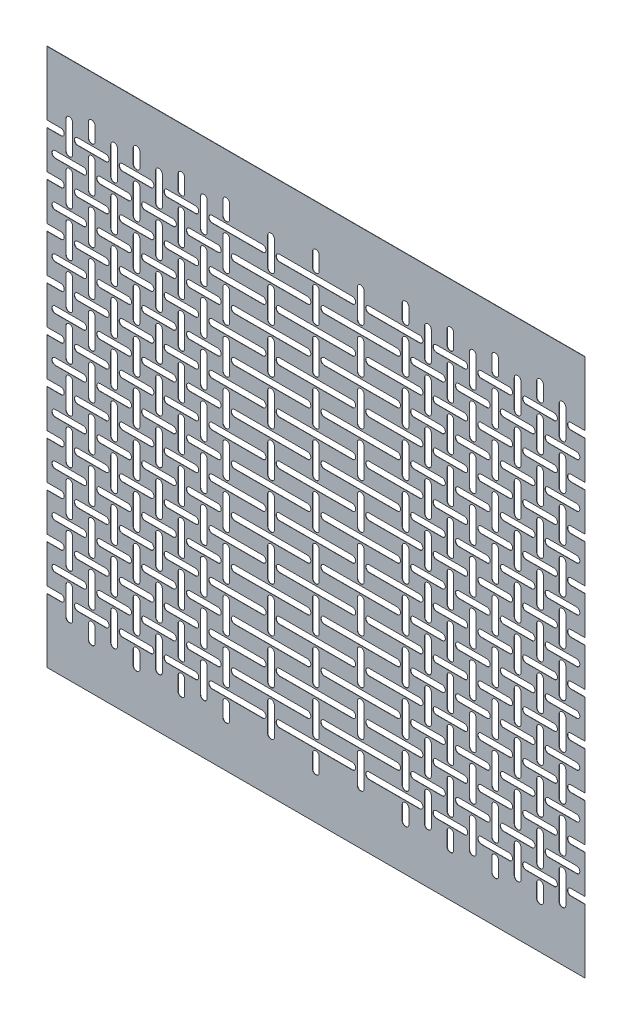
SolidWorks part; units mm, degrees
ref_plane "Front Plane" through (0, 0, 0) normal (0, 0, 1) x (1, 0, 0)
ref_plane "Top Plane" through (0, 0, 0) normal (0, 1, 0) x (1, 0, 0)
ref_plane "Right Plane" through (0, 0, 0) normal (1, 0, 0) x (0, 0, -1)
sketch "Model" plane through (0, 0, 0) normal (0, 0, 1) x (1, 0, 0)
  line L0 (0, 31.5) -> (6.25, 31.5)
  line L1 (0, 28.5) -> (6.25, 28.5)
  line L2 (13.75, 31.5) -> (26.25, 31.5)
  line L3 (13.75, 28.5) -> (26.25, 28.5)
  line L4 (33.75, 31.5) -> (46.25, 31.5)
  line L5 (33.75, 28.5) -> (46.25, 28.5)
  line L6 (53.75, 31.5) -> (66.25, 31.5)
  line L7 (53.75, 28.5) -> (66.25, 28.5)
  line L8 (73.75, 31.5) -> (80, 31.5)
  line L9 (73.75, 28.5) -> (80, 28.5)
  line L10 (3.75, 41.5) -> (16.25, 41.5)
  line L11 (3.75, 38.5) -> (16.25, 38.5)
  line L12 (23.75, 41.5) -> (36.25, 41.5)
  line L13 (23.75, 38.5) -> (36.25, 38.5)
  line L14 (43.75, 41.5) -> (56.25, 41.5)
  line L15 (43.75, 38.5) -> (56.25, 38.5)
  line L16 (63.75, 41.5) -> (76.25, 41.5)
  line L17 (63.75, 38.5) -> (76.25, 38.5)
  line L18 (0, 51.5) -> (6.25, 51.5)
  line L19 (0, 48.5) -> (6.25, 48.5)
  line L20 (13.75, 51.5) -> (26.25, 51.5)
  line L21 (13.75, 48.5) -> (26.25, 48.5)
  line L22 (33.75, 51.5) -> (46.25, 51.5)
  line L23 (33.75, 48.5) -> (46.25, 48.5)
  line L24 (53.75, 51.5) -> (66.25, 51.5)
  line L25 (53.75, 48.5) -> (66.25, 48.5)
  line L26 (73.75, 51.5) -> (80, 51.5)
  line L27 (73.75, 48.5) -> (80, 48.5)
  line L28 (3.75, 61.5) -> (16.25, 61.5)
  line L29 (3.75, 58.5) -> (16.25, 58.5)
  line L30 (23.75, 61.5) -> (36.25, 61.5)
  line L31 (23.75, 58.5) -> (36.25, 58.5)
  line L32 (43.75, 61.5) -> (56.25, 61.5)
  line L33 (43.75, 58.5) -> (56.25, 58.5)
  line L34 (63.75, 61.5) -> (76.25, 61.5)
  line L35 (63.75, 58.5) -> (76.25, 58.5)
  line L36 (0, 71.5) -> (6.25, 71.5)
  line L37 (0, 68.5) -> (6.25, 68.5)
  line L38 (13.75, 71.5) -> (26.25, 71.5)
  line L39 (13.75, 68.5) -> (26.25, 68.5)
  line L40 (33.75, 71.5) -> (46.25, 71.5)
  line L41 (33.75, 68.5) -> (46.25, 68.5)
  line L42 (53.75, 71.5) -> (66.25, 71.5)
  line L43 (53.75, 68.5) -> (66.25, 68.5)
  line L44 (73.75, 71.5) -> (80, 71.5)
  line L45 (73.75, 68.5) -> (80, 68.5)
  line L46 (3.75, 81.5) -> (16.25, 81.5)
  line L47 (3.75, 78.5) -> (16.25, 78.5)
  line L48 (23.75, 81.5) -> (36.25, 81.5)
  line L49 (23.75, 78.5) -> (36.25, 78.5)
  line L50 (43.75, 81.5) -> (56.25, 81.5)
  line L51 (43.75, 78.5) -> (56.25, 78.5)
  line L52 (63.75, 81.5) -> (76.25, 81.5)
  line L53 (63.75, 78.5) -> (76.25, 78.5)
  line L54 (0, 91.5) -> (6.25, 91.5)
  line L55 (0, 88.5) -> (6.25, 88.5)
  line L56 (13.75, 91.5) -> (26.25, 91.5)
  line L57 (13.75, 88.5) -> (26.25, 88.5)
  line L58 (33.75, 91.5) -> (46.25, 91.5)
  line L59 (33.75, 88.5) -> (46.25, 88.5)
  line L60 (53.75, 91.5) -> (66.25, 91.5)
  line L61 (53.75, 88.5) -> (66.25, 88.5)
  line L62 (73.75, 91.5) -> (80, 91.5)
  line L63 (73.75, 88.5) -> (80, 88.5)
  line L64 (3.75, 101.5) -> (16.25, 101.5)
  line L65 (3.75, 98.5) -> (16.25, 98.5)
  line L66 (23.75, 101.5) -> (36.25, 101.5)
  line L67 (23.75, 98.5) -> (36.25, 98.5)
  line L68 (43.75, 101.5) -> (56.25, 101.5)
  line L69 (43.75, 98.5) -> (56.25, 98.5)
  line L70 (63.75, 101.5) -> (76.25, 101.5)
  line L71 (63.75, 98.5) -> (76.25, 98.5)
  line L72 (0, 111.5) -> (6.25, 111.5)
  line L73 (0, 108.5) -> (6.25, 108.5)
  line L74 (13.75, 111.5) -> (26.25, 111.5)
  line L75 (13.75, 108.5) -> (26.25, 108.5)
  line L76 (33.75, 111.5) -> (46.25, 111.5)
  line L77 (33.75, 108.5) -> (46.25, 108.5)
  line L78 (53.75, 111.5) -> (66.25, 111.5)
  line L79 (53.75, 108.5) -> (66.25, 108.5)
  line L80 (73.75, 111.5) -> (80, 111.5)
  line L81 (73.75, 108.5) -> (80, 108.5)
  line L82 (3.75, 121.5) -> (16.25, 121.5)
  line L83 (3.75, 118.5) -> (16.25, 118.5)
  line L84 (23.75, 121.5) -> (36.25, 121.5)
  line L85 (23.75, 118.5) -> (36.25, 118.5)
  line L86 (43.75, 121.5) -> (56.25, 121.5)
  line L87 (43.75, 118.5) -> (56.25, 118.5)
  line L88 (63.75, 121.5) -> (76.25, 121.5)
  line L89 (63.75, 118.5) -> (76.25, 118.5)
  line L90 (0, 131.5) -> (6.25, 131.5)
  line L91 (0, 128.5) -> (6.25, 128.5)
  line L92 (13.75, 131.5) -> (26.25, 131.5)
  line L93 (13.75, 128.5) -> (26.25, 128.5)
  line L94 (33.75, 131.5) -> (46.25, 131.5)
  line L95 (33.75, 128.5) -> (46.25, 128.5)
  line L96 (53.75, 131.5) -> (66.25, 131.5)
  line L97 (53.75, 128.5) -> (66.25, 128.5)
  line L98 (73.75, 131.5) -> (80, 131.5)
  line L99 (73.75, 128.5) -> (80, 128.5)
  line L100 (3.75, 141.5) -> (16.25, 141.5)
  line L101 (3.75, 138.5) -> (16.25, 138.5)
  line L102 (23.75, 141.5) -> (36.25, 141.5)
  line L103 (23.75, 138.5) -> (36.25, 138.5)
  line L104 (43.75, 141.5) -> (56.25, 141.5)
  line L105 (43.75, 138.5) -> (56.25, 138.5)
  line L106 (63.75, 141.5) -> (76.25, 141.5)
  line L107 (63.75, 138.5) -> (76.25, 138.5)
  line L108 (0, 151.5) -> (6.25, 151.5)
  line L109 (0, 148.5) -> (6.25, 148.5)
  line L110 (13.75, 151.5) -> (26.25, 151.5)
  line L111 (13.75, 148.5) -> (26.25, 148.5)
  line L112 (33.75, 151.5) -> (46.25, 151.5)
  line L113 (33.75, 148.5) -> (46.25, 148.5)
  line L114 (53.75, 151.5) -> (66.25, 151.5)
  line L115 (53.75, 148.5) -> (66.25, 148.5)
  line L116 (73.75, 151.5) -> (80, 151.5)
  line L117 (73.75, 148.5) -> (80, 148.5)
  line L118 (3.75, 161.5) -> (16.25, 161.5)
  line L119 (3.75, 158.5) -> (16.25, 158.5)
  line L120 (23.75, 161.5) -> (36.25, 161.5)
  line L121 (23.75, 158.5) -> (36.25, 158.5)
  line L122 (43.75, 161.5) -> (56.25, 161.5)
  line L123 (43.75, 158.5) -> (56.25, 158.5)
  line L124 (63.75, 161.5) -> (76.25, 161.5)
  line L125 (63.75, 158.5) -> (76.25, 158.5)
  line L126 (0, 171.5) -> (6.25, 171.5)
  line L127 (0, 168.5) -> (6.25, 168.5)
  line L128 (13.75, 171.5) -> (26.25, 171.5)
  line L129 (13.75, 168.5) -> (26.25, 168.5)
  line L130 (33.75, 171.5) -> (46.25, 171.5)
  line L131 (33.75, 168.5) -> (46.25, 168.5)
  line L132 (53.75, 171.5) -> (66.25, 171.5)
  line L133 (53.75, 168.5) -> (66.25, 168.5)
  line L134 (73.75, 171.5) -> (80, 171.5)
  line L135 (73.75, 168.5) -> (80, 168.5)
  line L136 (3.75, 181.5) -> (16.25, 181.5)
  line L137 (3.75, 178.5) -> (16.25, 178.5)
  line L138 (23.75, 181.5) -> (36.25, 181.5)
  line L139 (23.75, 178.5) -> (36.25, 178.5)
  line L140 (43.75, 181.5) -> (56.25, 181.5)
  line L141 (43.75, 178.5) -> (56.25, 178.5)
  line L142 (63.75, 181.5) -> (76.25, 181.5)
  line L143 (63.75, 178.5) -> (76.25, 178.5)
  line L144 (0, 191.5) -> (6.25, 191.5)
  line L145 (0, 188.5) -> (6.25, 188.5)
  line L146 (13.75, 191.5) -> (26.25, 191.5)
  line L147 (13.75, 188.5) -> (26.25, 188.5)
  line L148 (33.75, 191.5) -> (46.25, 191.5)
  line L149 (33.75, 188.5) -> (46.25, 188.5)
  line L150 (53.75, 191.5) -> (66.25, 191.5)
  line L151 (53.75, 188.5) -> (66.25, 188.5)
  line L152 (73.75, 191.5) -> (80, 191.5)
  line L153 (73.75, 188.5) -> (80, 188.5)
  line L154 (3.75, 201.5) -> (16.25, 201.5)
  line L155 (3.75, 198.5) -> (16.25, 198.5)
  line L156 (23.75, 201.5) -> (36.25, 201.5)
  line L157 (23.75, 198.5) -> (36.25, 198.5)
  line L158 (43.75, 201.5) -> (56.25, 201.5)
  line L159 (43.75, 198.5) -> (56.25, 198.5)
  line L160 (63.75, 201.5) -> (76.25, 201.5)
  line L161 (63.75, 198.5) -> (76.25, 198.5)
  line L162 (0, 211.5) -> (6.25, 211.5)
  line L163 (0, 208.5) -> (6.25, 208.5)
  line L164 (13.75, 211.5) -> (26.25, 211.5)
  line L165 (13.75, 208.5) -> (26.25, 208.5)
  line L166 (33.75, 211.5) -> (46.25, 211.5)
  line L167 (33.75, 208.5) -> (46.25, 208.5)
  line L168 (53.75, 211.5) -> (66.25, 211.5)
  line L169 (53.75, 208.5) -> (66.25, 208.5)
  line L170 (73.75, 211.5) -> (80, 211.5)
  line L171 (73.75, 208.5) -> (80, 208.5)
  line L172 (11.5, 23.75) -> (11.5, 36.25)
  line L173 (8.5, 23.75) -> (8.5, 36.25)
  line L174 (11.5, 43.75) -> (11.5, 56.25)
  line L175 (8.5, 43.75) -> (8.5, 56.25)
  line L176 (11.5, 63.75) -> (11.5, 76.25)
  line L177 (8.5, 63.75) -> (8.5, 76.25)
  line L178 (11.5, 83.75) -> (11.5, 96.25)
  line L179 (8.5, 83.75) -> (8.5, 96.25)
  line L180 (11.5, 103.75) -> (11.5, 116.25)
  line L181 (8.5, 103.75) -> (8.5, 116.25)
  line L182 (11.5, 123.75) -> (11.5, 136.25)
  line L183 (8.5, 123.75) -> (8.5, 136.25)
  line L184 (11.5, 143.75) -> (11.5, 156.25)
  line L185 (8.5, 143.75) -> (8.5, 156.25)
  line L186 (11.5, 163.75) -> (11.5, 176.25)
  line L187 (8.5, 163.75) -> (8.5, 176.25)
  line L188 (11.5, 183.75) -> (11.5, 196.25)
  line L189 (8.5, 183.75) -> (8.5, 196.25)
  line L190 (11.5, 203.75) -> (11.5, 216.25)
  line L191 (8.5, 203.75) -> (8.5, 216.25)
  line L192 (21.5, 20) -> (21.5, 26.25)
  line L193 (18.5, 20) -> (18.5, 26.25)
  line L194 (21.5, 33.75) -> (21.5, 46.25)
  line L195 (18.5, 33.75) -> (18.5, 46.25)
  line L196 (21.5, 53.75) -> (21.5, 66.25)
  line L197 (18.5, 53.75) -> (18.5, 66.25)
  line L198 (21.5, 73.75) -> (21.5, 86.25)
  line L199 (18.5, 73.75) -> (18.5, 86.25)
  line L200 (21.5, 93.75) -> (21.5, 106.25)
  line L201 (18.5, 93.75) -> (18.5, 106.25)
  line L202 (21.5, 113.75) -> (21.5, 126.25)
  line L203 (18.5, 113.75) -> (18.5, 126.25)
  line L204 (21.5, 133.75) -> (21.5, 146.25)
  line L205 (18.5, 133.75) -> (18.5, 146.25)
  line L206 (21.5, 153.75) -> (21.5, 166.25)
  line L207 (18.5, 153.75) -> (18.5, 166.25)
  line L208 (21.5, 173.75) -> (21.5, 186.25)
  line L209 (18.5, 173.75) -> (18.5, 186.25)
  line L210 (21.5, 193.75) -> (21.5, 206.25)
  line L211 (18.5, 193.75) -> (18.5, 206.25)
  line L212 (21.5, 213.75) -> (21.5, 220)
  line L213 (18.5, 213.75) -> (18.5, 220)
  line L214 (31.5, 23.75) -> (31.5, 36.25)
  line L215 (28.5, 23.75) -> (28.5, 36.25)
  line L216 (31.5, 43.75) -> (31.5, 56.25)
  line L217 (28.5, 43.75) -> (28.5, 56.25)
  line L218 (31.5, 63.75) -> (31.5, 76.25)
  line L219 (28.5, 63.75) -> (28.5, 76.25)
  line L220 (31.5, 83.75) -> (31.5, 96.25)
  line L221 (28.5, 83.75) -> (28.5, 96.25)
  line L222 (31.5, 103.75) -> (31.5, 116.25)
  line L223 (28.5, 103.75) -> (28.5, 116.25)
  line L224 (31.5, 123.75) -> (31.5, 136.25)
  line L225 (28.5, 123.75) -> (28.5, 136.25)
  line L226 (31.5, 143.75) -> (31.5, 156.25)
  line L227 (28.5, 143.75) -> (28.5, 156.25)
  line L228 (31.5, 163.75) -> (31.5, 176.25)
  line L229 (28.5, 163.75) -> (28.5, 176.25)
  line L230 (31.5, 183.75) -> (31.5, 196.25)
  line L231 (28.5, 183.75) -> (28.5, 196.25)
  line L232 (31.5, 203.75) -> (31.5, 216.25)
  line L233 (28.5, 203.75) -> (28.5, 216.25)
  line L234 (41.5, 20) -> (41.5, 26.25)
  line L235 (38.5, 20) -> (38.5, 26.25)
  line L236 (41.5, 33.75) -> (41.5, 46.25)
  line L237 (38.5, 33.75) -> (38.5, 46.25)
  line L238 (41.5, 53.75) -> (41.5, 66.25)
  line L239 (38.5, 53.75) -> (38.5, 66.25)
  line L240 (41.5, 73.75) -> (41.5, 86.25)
  line L241 (38.5, 73.75) -> (38.5, 86.25)
  line L242 (41.5, 93.75) -> (41.5, 106.25)
  line L243 (38.5, 93.75) -> (38.5, 106.25)
  line L244 (41.5, 113.75) -> (41.5, 126.25)
  line L245 (38.5, 113.75) -> (38.5, 126.25)
  line L246 (41.5, 133.75) -> (41.5, 146.25)
  line L247 (38.5, 133.75) -> (38.5, 146.25)
  line L248 (41.5, 153.75) -> (41.5, 166.25)
  line L249 (38.5, 153.75) -> (38.5, 166.25)
  line L250 (41.5, 173.75) -> (41.5, 186.25)
  line L251 (38.5, 173.75) -> (38.5, 186.25)
  line L252 (41.5, 193.75) -> (41.5, 206.25)
  line L253 (38.5, 193.75) -> (38.5, 206.25)
  line L254 (41.5, 213.75) -> (41.5, 220)
  line L255 (38.5, 213.75) -> (38.5, 220)
  line L256 (51.5, 23.75) -> (51.5, 36.25)
  line L257 (48.5, 23.75) -> (48.5, 36.25)
  line L258 (51.5, 43.75) -> (51.5, 56.25)
  line L259 (48.5, 43.75) -> (48.5, 56.25)
  line L260 (51.5, 63.75) -> (51.5, 76.25)
  line L261 (48.5, 63.75) -> (48.5, 76.25)
  line L262 (51.5, 83.75) -> (51.5, 96.25)
  line L263 (48.5, 83.75) -> (48.5, 96.25)
  line L264 (51.5, 103.75) -> (51.5, 116.25)
  line L265 (48.5, 103.75) -> (48.5, 116.25)
  line L266 (51.5, 123.75) -> (51.5, 136.25)
  line L267 (48.5, 123.75) -> (48.5, 136.25)
  line L268 (51.5, 143.75) -> (51.5, 156.25)
  line L269 (48.5, 143.75) -> (48.5, 156.25)
  line L270 (51.5, 163.75) -> (51.5, 176.25)
  line L271 (48.5, 163.75) -> (48.5, 176.25)
  line L272 (51.5, 183.75) -> (51.5, 196.25)
  line L273 (48.5, 183.75) -> (48.5, 196.25)
  line L274 (51.5, 203.75) -> (51.5, 216.25)
  line L275 (48.5, 203.75) -> (48.5, 216.25)
  line L276 (61.5, 20) -> (61.5, 26.25)
  line L277 (58.5, 20) -> (58.5, 26.25)
  line L278 (61.5, 33.75) -> (61.5, 46.25)
  line L279 (58.5, 33.75) -> (58.5, 46.25)
  line L280 (61.5, 53.75) -> (61.5, 66.25)
  line L281 (58.5, 53.75) -> (58.5, 66.25)
  line L282 (61.5, 73.75) -> (61.5, 86.25)
  line L283 (58.5, 73.75) -> (58.5, 86.25)
  line L284 (61.5, 93.75) -> (61.5, 106.25)
  line L285 (58.5, 93.75) -> (58.5, 106.25)
  line L286 (61.5, 113.75) -> (61.5, 126.25)
  line L287 (58.5, 113.75) -> (58.5, 126.25)
  line L288 (61.5, 133.75) -> (61.5, 146.25)
  line L289 (58.5, 133.75) -> (58.5, 146.25)
  line L290 (61.5, 153.75) -> (61.5, 166.25)
  line L291 (58.5, 153.75) -> (58.5, 166.25)
  line L292 (61.5, 173.75) -> (61.5, 186.25)
  line L293 (58.5, 173.75) -> (58.5, 186.25)
  line L294 (61.5, 193.75) -> (61.5, 206.25)
  line L295 (58.5, 193.75) -> (58.5, 206.25)
  line L296 (61.5, 213.75) -> (61.5, 220)
  line L297 (58.5, 213.75) -> (58.5, 220)
  line L298 (71.5, 23.75) -> (71.5, 36.25)
  line L299 (68.5, 23.75) -> (68.5, 36.25)
  line L300 (71.5, 43.75) -> (71.5, 56.25)
  line L301 (68.5, 43.75) -> (68.5, 56.25)
  line L302 (71.5, 63.75) -> (71.5, 76.25)
  line L303 (68.5, 63.75) -> (68.5, 76.25)
  line L304 (71.5, 83.75) -> (71.5, 96.25)
  line L305 (68.5, 83.75) -> (68.5, 96.25)
  line L306 (71.5, 103.75) -> (71.5, 116.25)
  line L307 (68.5, 103.75) -> (68.5, 116.25)
  line L308 (71.5, 123.75) -> (71.5, 136.25)
  line L309 (68.5, 123.75) -> (68.5, 136.25)
  line L310 (71.5, 143.75) -> (71.5, 156.25)
  line L311 (68.5, 143.75) -> (68.5, 156.25)
  line L312 (71.5, 163.75) -> (71.5, 176.25)
  line L313 (68.5, 163.75) -> (68.5, 176.25)
  line L314 (71.5, 183.75) -> (71.5, 196.25)
  line L315 (68.5, 183.75) -> (68.5, 196.25)
  line L316 (71.5, 203.75) -> (71.5, 216.25)
  line L317 (68.5, 203.75) -> (68.5, 216.25)
  line L318 (81.5, 20) -> (81.5, 26.25)
  line L319 (78.5, 20) -> (78.5, 26.25)
  line L320 (81.5, 33.75) -> (81.5, 46.25)
  line L321 (78.5, 33.75) -> (78.5, 46.25)
  line L322 (81.5, 53.75) -> (81.5, 66.25)
  line L323 (78.5, 53.75) -> (78.5, 66.25)
  line L324 (81.5, 73.75) -> (81.5, 86.25)
  line L325 (78.5, 73.75) -> (78.5, 86.25)
  line L326 (81.5, 93.75) -> (81.5, 106.25)
  line L327 (78.5, 93.75) -> (78.5, 106.25)
  line L328 (81.5, 113.75) -> (81.5, 126.25)
  line L329 (78.5, 113.75) -> (78.5, 126.25)
  line L330 (81.5, 133.75) -> (81.5, 146.25)
  line L331 (78.5, 133.75) -> (78.5, 146.25)
  line L332 (81.5, 153.75) -> (81.5, 166.25)
  line L333 (78.5, 153.75) -> (78.5, 166.25)
  line L334 (81.5, 173.75) -> (81.5, 186.25)
  line L335 (78.5, 173.75) -> (78.5, 186.25)
  line L336 (81.5, 193.75) -> (81.5, 206.25)
  line L337 (78.5, 193.75) -> (78.5, 206.25)
  line L338 (81.5, 213.75) -> (81.5, 220)
  line L339 (78.5, 213.75) -> (78.5, 220)
  line L340 (0, 0) -> (80, 0)
  line L341 (80, 240) -> (0, 240)
  line L342 (0, 0) -> (0, 28.5)
  line L343 (0, 31.5) -> (0, 48.5)
  line L344 (0, 51.5) -> (0, 68.5)
  line L345 (0, 71.5) -> (0, 88.5)
  line L346 (0, 91.5) -> (0, 108.5)
  line L347 (0, 111.5) -> (0, 128.5)
  line L348 (0, 131.5) -> (0, 148.5)
  line L349 (0, 151.5) -> (0, 168.5)
  line L350 (0, 171.5) -> (0, 188.5)
  line L351 (0, 191.5) -> (0, 208.5)
  line L352 (0, 211.5) -> (0, 240)
  line L353 (80, 31.5) -> (96.25, 31.5)
  line L354 (80, 28.5) -> (96.25, 28.5)
  line L355 (103.75, 31.5) -> (136.25, 31.5)
  line L356 (103.75, 28.5) -> (136.25, 28.5)
  line L357 (143.75, 31.5) -> (160, 31.5)
  line L358 (143.75, 28.5) -> (160, 28.5)
  line L359 (83.75, 41.5) -> (116.25, 41.5)
  line L360 (83.75, 38.5) -> (116.25, 38.5)
  line L361 (123.75, 41.5) -> (156.25, 41.5)
  line L362 (123.75, 38.5) -> (156.25, 38.5)
  line L363 (80, 51.5) -> (96.25, 51.5)
  line L364 (80, 48.5) -> (96.25, 48.5)
  line L365 (103.75, 51.5) -> (136.25, 51.5)
  line L366 (103.75, 48.5) -> (136.25, 48.5)
  line L367 (143.75, 51.5) -> (160, 51.5)
  line L368 (143.75, 48.5) -> (160, 48.5)
  line L369 (83.75, 61.5) -> (116.25, 61.5)
  line L370 (83.75, 58.5) -> (116.25, 58.5)
  line L371 (123.75, 61.5) -> (156.25, 61.5)
  line L372 (123.75, 58.5) -> (156.25, 58.5)
  line L373 (80, 71.5) -> (96.25, 71.5)
  line L374 (80, 68.5) -> (96.25, 68.5)
  line L375 (103.75, 71.5) -> (136.25, 71.5)
  line L376 (103.75, 68.5) -> (136.25, 68.5)
  line L377 (143.75, 71.5) -> (160, 71.5)
  line L378 (143.75, 68.5) -> (160, 68.5)
  line L379 (83.75, 81.5) -> (116.25, 81.5)
  line L380 (83.75, 78.5) -> (116.25, 78.5)
  line L381 (123.75, 81.5) -> (156.25, 81.5)
  line L382 (123.75, 78.5) -> (156.25, 78.5)
  line L383 (80, 91.5) -> (96.25, 91.5)
  line L384 (80, 88.5) -> (96.25, 88.5)
  line L385 (103.75, 91.5) -> (136.25, 91.5)
  line L386 (103.75, 88.5) -> (136.25, 88.5)
  line L387 (143.75, 91.5) -> (160, 91.5)
  line L388 (143.75, 88.5) -> (160, 88.5)
  line L389 (83.75, 101.5) -> (116.25, 101.5)
  line L390 (83.75, 98.5) -> (116.25, 98.5)
  line L391 (123.75, 101.5) -> (156.25, 101.5)
  line L392 (123.75, 98.5) -> (156.25, 98.5)
  line L393 (80, 111.5) -> (96.25, 111.5)
  line L394 (80, 108.5) -> (96.25, 108.5)
  line L395 (103.75, 111.5) -> (136.25, 111.5)
  line L396 (103.75, 108.5) -> (136.25, 108.5)
  line L397 (143.75, 111.5) -> (160, 111.5)
  line L398 (143.75, 108.5) -> (160, 108.5)
  line L399 (83.75, 121.5) -> (116.25, 121.5)
  line L400 (83.75, 118.5) -> (116.25, 118.5)
  line L401 (123.75, 121.5) -> (156.25, 121.5)
  line L402 (123.75, 118.5) -> (156.25, 118.5)
  line L403 (80, 131.5) -> (96.25, 131.5)
  line L404 (80, 128.5) -> (96.25, 128.5)
  line L405 (103.75, 131.5) -> (136.25, 131.5)
  line L406 (103.75, 128.5) -> (136.25, 128.5)
  line L407 (143.75, 131.5) -> (160, 131.5)
  line L408 (143.75, 128.5) -> (160, 128.5)
  line L409 (83.75, 141.5) -> (116.25, 141.5)
  line L410 (83.75, 138.5) -> (116.25, 138.5)
  line L411 (123.75, 141.5) -> (156.25, 141.5)
  line L412 (123.75, 138.5) -> (156.25, 138.5)
  line L413 (80, 151.5) -> (96.25, 151.5)
  line L414 (80, 148.5) -> (96.25, 148.5)
  line L415 (103.75, 151.5) -> (136.25, 151.5)
  line L416 (103.75, 148.5) -> (136.25, 148.5)
  line L417 (143.75, 151.5) -> (160, 151.5)
  line L418 (143.75, 148.5) -> (160, 148.5)
  line L419 (83.75, 161.5) -> (116.25, 161.5)
  line L420 (83.75, 158.5) -> (116.25, 158.5)
  line L421 (123.75, 161.5) -> (156.25, 161.5)
  line L422 (123.75, 158.5) -> (156.25, 158.5)
  line L423 (80, 171.5) -> (96.25, 171.5)
  line L424 (80, 168.5) -> (96.25, 168.5)
  line L425 (103.75, 171.5) -> (136.25, 171.5)
  line L426 (103.75, 168.5) -> (136.25, 168.5)
  line L427 (143.75, 171.5) -> (160, 171.5)
  line L428 (143.75, 168.5) -> (160, 168.5)
  line L429 (83.75, 181.5) -> (116.25, 181.5)
  line L430 (83.75, 178.5) -> (116.25, 178.5)
  line L431 (123.75, 181.5) -> (156.25, 181.5)
  line L432 (123.75, 178.5) -> (156.25, 178.5)
  line L433 (80, 191.5) -> (96.25, 191.5)
  line L434 (80, 188.5) -> (96.25, 188.5)
  line L435 (103.75, 191.5) -> (136.25, 191.5)
  line L436 (103.75, 188.5) -> (136.25, 188.5)
  line L437 (143.75, 191.5) -> (160, 191.5)
  line L438 (143.75, 188.5) -> (160, 188.5)
  line L439 (83.75, 201.5) -> (116.25, 201.5)
  line L440 (83.75, 198.5) -> (116.25, 198.5)
  line L441 (123.75, 201.5) -> (156.25, 201.5)
  line L442 (123.75, 198.5) -> (156.25, 198.5)
  line L443 (80, 211.5) -> (96.25, 211.5)
  line L444 (80, 208.5) -> (96.25, 208.5)
  line L445 (103.75, 211.5) -> (136.25, 211.5)
  line L446 (103.75, 208.5) -> (136.25, 208.5)
  line L447 (143.75, 211.5) -> (160, 211.5)
  line L448 (143.75, 208.5) -> (160, 208.5)
  line L449 (101.5, 23.75) -> (101.5, 36.25)
  line L450 (98.5, 23.75) -> (98.5, 36.25)
  line L451 (101.5, 43.75) -> (101.5, 56.25)
  line L452 (98.5, 43.75) -> (98.5, 56.25)
  line L453 (101.5, 63.75) -> (101.5, 76.25)
  line L454 (98.5, 63.75) -> (98.5, 76.25)
  line L455 (101.5, 83.75) -> (101.5, 96.25)
  line L456 (98.5, 83.75) -> (98.5, 96.25)
  line L457 (101.5, 103.75) -> (101.5, 116.25)
  line L458 (98.5, 103.75) -> (98.5, 116.25)
  line L459 (101.5, 123.75) -> (101.5, 136.25)
  line L460 (98.5, 123.75) -> (98.5, 136.25)
  line L461 (101.5, 143.75) -> (101.5, 156.25)
  line L462 (98.5, 143.75) -> (98.5, 156.25)
  line L463 (101.5, 163.75) -> (101.5, 176.25)
  line L464 (98.5, 163.75) -> (98.5, 176.25)
  line L465 (101.5, 183.75) -> (101.5, 196.25)
  line L466 (98.5, 183.75) -> (98.5, 196.25)
  line L467 (101.5, 203.75) -> (101.5, 216.25)
  line L468 (98.5, 203.75) -> (98.5, 216.25)
  line L469 (121.5, 20) -> (121.5, 26.25)
  line L470 (118.5, 20) -> (118.5, 26.25)
  line L471 (121.5, 33.75) -> (121.5, 46.25)
  line L472 (118.5, 33.75) -> (118.5, 46.25)
  line L473 (121.5, 53.75) -> (121.5, 66.25)
  line L474 (118.5, 53.75) -> (118.5, 66.25)
  line L475 (121.5, 73.75) -> (121.5, 86.25)
  line L476 (118.5, 73.75) -> (118.5, 86.25)
  line L477 (121.5, 93.75) -> (121.5, 106.25)
  line L478 (118.5, 93.75) -> (118.5, 106.25)
  line L479 (121.5, 113.75) -> (121.5, 126.25)
  line L480 (118.5, 113.75) -> (118.5, 126.25)
  line L481 (121.5, 133.75) -> (121.5, 146.25)
  line L482 (118.5, 133.75) -> (118.5, 146.25)
  line L483 (121.5, 153.75) -> (121.5, 166.25)
  line L484 (118.5, 153.75) -> (118.5, 166.25)
  line L485 (121.5, 173.75) -> (121.5, 186.25)
  line L486 (118.5, 173.75) -> (118.5, 186.25)
  line L487 (121.5, 193.75) -> (121.5, 206.25)
  line L488 (118.5, 193.75) -> (118.5, 206.25)
  line L489 (121.5, 213.75) -> (121.5, 220)
  line L490 (118.5, 213.75) -> (118.5, 220)
  line L491 (141.5, 23.75) -> (141.5, 36.25)
  line L492 (138.5, 23.75) -> (138.5, 36.25)
  line L493 (141.5, 43.75) -> (141.5, 56.25)
  line L494 (138.5, 43.75) -> (138.5, 56.25)
  line L495 (141.5, 63.75) -> (141.5, 76.25)
  line L496 (138.5, 63.75) -> (138.5, 76.25)
  line L497 (141.5, 83.75) -> (141.5, 96.25)
  line L498 (138.5, 83.75) -> (138.5, 96.25)
  line L499 (141.5, 103.75) -> (141.5, 116.25)
  line L500 (138.5, 103.75) -> (138.5, 116.25)
  line L501 (141.5, 123.75) -> (141.5, 136.25)
  line L502 (138.5, 123.75) -> (138.5, 136.25)
  line L503 (141.5, 143.75) -> (141.5, 156.25)
  line L504 (138.5, 143.75) -> (138.5, 156.25)
  line L505 (141.5, 163.75) -> (141.5, 176.25)
  line L506 (138.5, 163.75) -> (138.5, 176.25)
  line L507 (141.5, 183.75) -> (141.5, 196.25)
  line L508 (138.5, 183.75) -> (138.5, 196.25)
  line L509 (141.5, 203.75) -> (141.5, 216.25)
  line L510 (138.5, 203.75) -> (138.5, 216.25)
  line L511 (161.5, 20) -> (161.5, 26.25)
  line L512 (158.5, 20) -> (158.5, 26.25)
  line L513 (161.5, 33.75) -> (161.5, 46.25)
  line L514 (158.5, 33.75) -> (158.5, 46.25)
  line L515 (161.5, 53.75) -> (161.5, 66.25)
  line L516 (158.5, 53.75) -> (158.5, 66.25)
  line L517 (161.5, 73.75) -> (161.5, 86.25)
  line L518 (158.5, 73.75) -> (158.5, 86.25)
  line L519 (161.5, 93.75) -> (161.5, 106.25)
  line L520 (158.5, 93.75) -> (158.5, 106.25)
  line L521 (161.5, 113.75) -> (161.5, 126.25)
  line L522 (158.5, 113.75) -> (158.5, 126.25)
  line L523 (161.5, 133.75) -> (161.5, 146.25)
  line L524 (158.5, 133.75) -> (158.5, 146.25)
  line L525 (161.5, 153.75) -> (161.5, 166.25)
  line L526 (158.5, 153.75) -> (158.5, 166.25)
  line L527 (161.5, 173.75) -> (161.5, 186.25)
  line L528 (158.5, 173.75) -> (158.5, 186.25)
  line L529 (161.5, 193.75) -> (161.5, 206.25)
  line L530 (158.5, 193.75) -> (158.5, 206.25)
  line L531 (161.5, 213.75) -> (161.5, 220)
  line L532 (158.5, 213.75) -> (158.5, 220)
  line L533 (80, 0) -> (160, 0)
  line L534 (160, 240) -> (80, 240)
  line L535 (160, 31.5) -> (166.25, 31.5)
  line L536 (160, 28.5) -> (166.25, 28.5)
  line L537 (173.75, 31.5) -> (186.25, 31.5)
  line L538 (173.75, 28.5) -> (186.25, 28.5)
  line L539 (193.75, 31.5) -> (206.25, 31.5)
  line L540 (193.75, 28.5) -> (206.25, 28.5)
  line L541 (213.75, 31.5) -> (226.25, 31.5)
  line L542 (213.75, 28.5) -> (226.25, 28.5)
  line L543 (233.75, 31.5) -> (240, 31.5)
  line L544 (233.75, 28.5) -> (240, 28.5)
  line L545 (163.75, 41.5) -> (176.25, 41.5)
  line L546 (163.75, 38.5) -> (176.25, 38.5)
  line L547 (183.75, 41.5) -> (196.25, 41.5)
  line L548 (183.75, 38.5) -> (196.25, 38.5)
  line L549 (203.75, 41.5) -> (216.25, 41.5)
  line L550 (203.75, 38.5) -> (216.25, 38.5)
  line L551 (223.75, 41.5) -> (236.25, 41.5)
  line L552 (223.75, 38.5) -> (236.25, 38.5)
  line L553 (160, 51.5) -> (166.25, 51.5)
  line L554 (160, 48.5) -> (166.25, 48.5)
  line L555 (173.75, 51.5) -> (186.25, 51.5)
  line L556 (173.75, 48.5) -> (186.25, 48.5)
  line L557 (193.75, 51.5) -> (206.25, 51.5)
  line L558 (193.75, 48.5) -> (206.25, 48.5)
  line L559 (213.75, 51.5) -> (226.25, 51.5)
  line L560 (213.75, 48.5) -> (226.25, 48.5)
  line L561 (233.75, 51.5) -> (240, 51.5)
  line L562 (233.75, 48.5) -> (240, 48.5)
  line L563 (163.75, 61.5) -> (176.25, 61.5)
  line L564 (163.75, 58.5) -> (176.25, 58.5)
  line L565 (183.75, 61.5) -> (196.25, 61.5)
  line L566 (183.75, 58.5) -> (196.25, 58.5)
  line L567 (203.75, 61.5) -> (216.25, 61.5)
  line L568 (203.75, 58.5) -> (216.25, 58.5)
  line L569 (223.75, 61.5) -> (236.25, 61.5)
  line L570 (223.75, 58.5) -> (236.25, 58.5)
  line L571 (160, 71.5) -> (166.25, 71.5)
  line L572 (160, 68.5) -> (166.25, 68.5)
  line L573 (173.75, 71.5) -> (186.25, 71.5)
  line L574 (173.75, 68.5) -> (186.25, 68.5)
  line L575 (193.75, 71.5) -> (206.25, 71.5)
  line L576 (193.75, 68.5) -> (206.25, 68.5)
  line L577 (213.75, 71.5) -> (226.25, 71.5)
  line L578 (213.75, 68.5) -> (226.25, 68.5)
  line L579 (233.75, 71.5) -> (240, 71.5)
  line L580 (233.75, 68.5) -> (240, 68.5)
  line L581 (163.75, 81.5) -> (176.25, 81.5)
  line L582 (163.75, 78.5) -> (176.25, 78.5)
  line L583 (183.75, 81.5) -> (196.25, 81.5)
  line L584 (183.75, 78.5) -> (196.25, 78.5)
  line L585 (203.75, 81.5) -> (216.25, 81.5)
  line L586 (203.75, 78.5) -> (216.25, 78.5)
  line L587 (223.75, 81.5) -> (236.25, 81.5)
  line L588 (223.75, 78.5) -> (236.25, 78.5)
  line L589 (160, 91.5) -> (166.25, 91.5)
  line L590 (160, 88.5) -> (166.25, 88.5)
  line L591 (173.75, 91.5) -> (186.25, 91.5)
  line L592 (173.75, 88.5) -> (186.25, 88.5)
  line L593 (193.75, 91.5) -> (206.25, 91.5)
  line L594 (193.75, 88.5) -> (206.25, 88.5)
  line L595 (213.75, 91.5) -> (226.25, 91.5)
  line L596 (213.75, 88.5) -> (226.25, 88.5)
  line L597 (233.75, 91.5) -> (240, 91.5)
  line L598 (233.75, 88.5) -> (240, 88.5)
  line L599 (163.75, 101.5) -> (176.25, 101.5)
  line L600 (163.75, 98.5) -> (176.25, 98.5)
  line L601 (183.75, 101.5) -> (196.25, 101.5)
  line L602 (183.75, 98.5) -> (196.25, 98.5)
  line L603 (203.75, 101.5) -> (216.25, 101.5)
  line L604 (203.75, 98.5) -> (216.25, 98.5)
  line L605 (223.75, 101.5) -> (236.25, 101.5)
  line L606 (223.75, 98.5) -> (236.25, 98.5)
  line L607 (160, 111.5) -> (166.25, 111.5)
  line L608 (160, 108.5) -> (166.25, 108.5)
  line L609 (173.75, 111.5) -> (186.25, 111.5)
  line L610 (173.75, 108.5) -> (186.25, 108.5)
  line L611 (193.75, 111.5) -> (206.25, 111.5)
  line L612 (193.75, 108.5) -> (206.25, 108.5)
  line L613 (213.75, 111.5) -> (226.25, 111.5)
  line L614 (213.75, 108.5) -> (226.25, 108.5)
  line L615 (233.75, 111.5) -> (240, 111.5)
  line L616 (233.75, 108.5) -> (240, 108.5)
  line L617 (163.75, 121.5) -> (176.25, 121.5)
  line L618 (163.75, 118.5) -> (176.25, 118.5)
  line L619 (183.75, 121.5) -> (196.25, 121.5)
  line L620 (183.75, 118.5) -> (196.25, 118.5)
  line L621 (203.75, 121.5) -> (216.25, 121.5)
  line L622 (203.75, 118.5) -> (216.25, 118.5)
  line L623 (223.75, 121.5) -> (236.25, 121.5)
  line L624 (223.75, 118.5) -> (236.25, 118.5)
  line L625 (160, 131.5) -> (166.25, 131.5)
  line L626 (160, 128.5) -> (166.25, 128.5)
  line L627 (173.75, 131.5) -> (186.25, 131.5)
  line L628 (173.75, 128.5) -> (186.25, 128.5)
  line L629 (193.75, 131.5) -> (206.25, 131.5)
  line L630 (193.75, 128.5) -> (206.25, 128.5)
  line L631 (213.75, 131.5) -> (226.25, 131.5)
  line L632 (213.75, 128.5) -> (226.25, 128.5)
  line L633 (233.75, 131.5) -> (240, 131.5)
  line L634 (233.75, 128.5) -> (240, 128.5)
  line L635 (163.75, 141.5) -> (176.25, 141.5)
  line L636 (163.75, 138.5) -> (176.25, 138.5)
  line L637 (183.75, 141.5) -> (196.25, 141.5)
  line L638 (183.75, 138.5) -> (196.25, 138.5)
  line L639 (203.75, 141.5) -> (216.25, 141.5)
  line L640 (203.75, 138.5) -> (216.25, 138.5)
  line L641 (223.75, 141.5) -> (236.25, 141.5)
  line L642 (223.75, 138.5) -> (236.25, 138.5)
  line L643 (160, 151.5) -> (166.25, 151.5)
  line L644 (160, 148.5) -> (166.25, 148.5)
  line L645 (173.75, 151.5) -> (186.25, 151.5)
  line L646 (173.75, 148.5) -> (186.25, 148.5)
  line L647 (193.75, 151.5) -> (206.25, 151.5)
  line L648 (193.75, 148.5) -> (206.25, 148.5)
  line L649 (213.75, 151.5) -> (226.25, 151.5)
  line L650 (213.75, 148.5) -> (226.25, 148.5)
  line L651 (233.75, 151.5) -> (240, 151.5)
  line L652 (233.75, 148.5) -> (240, 148.5)
  line L653 (163.75, 161.5) -> (176.25, 161.5)
  line L654 (163.75, 158.5) -> (176.25, 158.5)
  line L655 (183.75, 161.5) -> (196.25, 161.5)
  line L656 (183.75, 158.5) -> (196.25, 158.5)
  line L657 (203.75, 161.5) -> (216.25, 161.5)
  line L658 (203.75, 158.5) -> (216.25, 158.5)
  line L659 (223.75, 161.5) -> (236.25, 161.5)
  line L660 (223.75, 158.5) -> (236.25, 158.5)
  line L661 (160, 171.5) -> (166.25, 171.5)
  line L662 (160, 168.5) -> (166.25, 168.5)
  line L663 (173.75, 171.5) -> (186.25, 171.5)
  line L664 (173.75, 168.5) -> (186.25, 168.5)
  line L665 (193.75, 171.5) -> (206.25, 171.5)
  line L666 (193.75, 168.5) -> (206.25, 168.5)
  line L667 (213.75, 171.5) -> (226.25, 171.5)
  line L668 (213.75, 168.5) -> (226.25, 168.5)
  line L669 (233.75, 171.5) -> (240, 171.5)
  line L670 (233.75, 168.5) -> (240, 168.5)
  line L671 (163.75, 181.5) -> (176.25, 181.5)
  line L672 (163.75, 178.5) -> (176.25, 178.5)
  line L673 (183.75, 181.5) -> (196.25, 181.5)
  line L674 (183.75, 178.5) -> (196.25, 178.5)
  line L675 (203.75, 181.5) -> (216.25, 181.5)
  line L676 (203.75, 178.5) -> (216.25, 178.5)
  line L677 (223.75, 181.5) -> (236.25, 181.5)
  line L678 (223.75, 178.5) -> (236.25, 178.5)
  line L679 (160, 191.5) -> (166.25, 191.5)
  line L680 (160, 188.5) -> (166.25, 188.5)
  line L681 (173.75, 191.5) -> (186.25, 191.5)
  line L682 (173.75, 188.5) -> (186.25, 188.5)
  line L683 (193.75, 191.5) -> (206.25, 191.5)
  line L684 (193.75, 188.5) -> (206.25, 188.5)
  line L685 (213.75, 191.5) -> (226.25, 191.5)
  line L686 (213.75, 188.5) -> (226.25, 188.5)
  line L687 (233.75, 191.5) -> (240, 191.5)
  line L688 (233.75, 188.5) -> (240, 188.5)
  line L689 (163.75, 201.5) -> (176.25, 201.5)
  line L690 (163.75, 198.5) -> (176.25, 198.5)
  line L691 (183.75, 201.5) -> (196.25, 201.5)
  line L692 (183.75, 198.5) -> (196.25, 198.5)
  line L693 (203.75, 201.5) -> (216.25, 201.5)
  line L694 (203.75, 198.5) -> (216.25, 198.5)
  line L695 (223.75, 201.5) -> (236.25, 201.5)
  line L696 (223.75, 198.5) -> (236.25, 198.5)
  line L697 (160, 211.5) -> (166.25, 211.5)
  line L698 (160, 208.5) -> (166.25, 208.5)
  line L699 (173.75, 211.5) -> (186.25, 211.5)
  line L700 (173.75, 208.5) -> (186.25, 208.5)
  line L701 (193.75, 211.5) -> (206.25, 211.5)
  line L702 (193.75, 208.5) -> (206.25, 208.5)
  line L703 (213.75, 211.5) -> (226.25, 211.5)
  line L704 (213.75, 208.5) -> (226.25, 208.5)
  line L705 (233.75, 211.5) -> (240, 211.5)
  line L706 (233.75, 208.5) -> (240, 208.5)
  line L707 (171.5, 23.75) -> (171.5, 36.25)
  line L708 (168.5, 23.75) -> (168.5, 36.25)
  line L709 (171.5, 43.75) -> (171.5, 56.25)
  line L710 (168.5, 43.75) -> (168.5, 56.25)
  line L711 (171.5, 63.75) -> (171.5, 76.25)
  line L712 (168.5, 63.75) -> (168.5, 76.25)
  line L713 (171.5, 83.75) -> (171.5, 96.25)
  line L714 (168.5, 83.75) -> (168.5, 96.25)
  line L715 (171.5, 103.75) -> (171.5, 116.25)
  line L716 (168.5, 103.75) -> (168.5, 116.25)
  line L717 (171.5, 123.75) -> (171.5, 136.25)
  line L718 (168.5, 123.75) -> (168.5, 136.25)
  line L719 (171.5, 143.75) -> (171.5, 156.25)
  line L720 (168.5, 143.75) -> (168.5, 156.25)
  line L721 (171.5, 163.75) -> (171.5, 176.25)
  line L722 (168.5, 163.75) -> (168.5, 176.25)
  line L723 (171.5, 183.75) -> (171.5, 196.25)
  line L724 (168.5, 183.75) -> (168.5, 196.25)
  line L725 (171.5, 203.75) -> (171.5, 216.25)
  line L726 (168.5, 203.75) -> (168.5, 216.25)
  line L727 (181.5, 20) -> (181.5, 26.25)
  line L728 (178.5, 20) -> (178.5, 26.25)
  line L729 (181.5, 33.75) -> (181.5, 46.25)
  line L730 (178.5, 33.75) -> (178.5, 46.25)
  line L731 (181.5, 53.75) -> (181.5, 66.25)
  line L732 (178.5, 53.75) -> (178.5, 66.25)
  line L733 (181.5, 73.75) -> (181.5, 86.25)
  line L734 (178.5, 73.75) -> (178.5, 86.25)
  line L735 (181.5, 93.75) -> (181.5, 106.25)
  line L736 (178.5, 93.75) -> (178.5, 106.25)
  line L737 (181.5, 113.75) -> (181.5, 126.25)
  line L738 (178.5, 113.75) -> (178.5, 126.25)
  line L739 (181.5, 133.75) -> (181.5, 146.25)
  line L740 (178.5, 133.75) -> (178.5, 146.25)
  line L741 (181.5, 153.75) -> (181.5, 166.25)
  line L742 (178.5, 153.75) -> (178.5, 166.25)
  line L743 (181.5, 173.75) -> (181.5, 186.25)
  line L744 (178.5, 173.75) -> (178.5, 186.25)
  line L745 (181.5, 193.75) -> (181.5, 206.25)
  line L746 (178.5, 193.75) -> (178.5, 206.25)
  line L747 (181.5, 213.75) -> (181.5, 220)
  line L748 (178.5, 213.75) -> (178.5, 220)
  line L749 (191.5, 23.75) -> (191.5, 36.25)
  line L750 (188.5, 23.75) -> (188.5, 36.25)
  line L751 (191.5, 43.75) -> (191.5, 56.25)
  line L752 (188.5, 43.75) -> (188.5, 56.25)
  line L753 (191.5, 63.75) -> (191.5, 76.25)
  line L754 (188.5, 63.75) -> (188.5, 76.25)
  line L755 (191.5, 83.75) -> (191.5, 96.25)
  line L756 (188.5, 83.75) -> (188.5, 96.25)
  line L757 (191.5, 103.75) -> (191.5, 116.25)
  line L758 (188.5, 103.75) -> (188.5, 116.25)
  line L759 (191.5, 123.75) -> (191.5, 136.25)
  line L760 (188.5, 123.75) -> (188.5, 136.25)
  line L761 (191.5, 143.75) -> (191.5, 156.25)
  line L762 (188.5, 143.75) -> (188.5, 156.25)
  line L763 (191.5, 163.75) -> (191.5, 176.25)
  line L764 (188.5, 163.75) -> (188.5, 176.25)
  line L765 (191.5, 183.75) -> (191.5, 196.25)
  line L766 (188.5, 183.75) -> (188.5, 196.25)
  line L767 (191.5, 203.75) -> (191.5, 216.25)
  line L768 (188.5, 203.75) -> (188.5, 216.25)
  line L769 (201.5, 20) -> (201.5, 26.25)
  line L770 (198.5, 20) -> (198.5, 26.25)
  line L771 (201.5, 33.75) -> (201.5, 46.25)
  line L772 (198.5, 33.75) -> (198.5, 46.25)
  line L773 (201.5, 53.75) -> (201.5, 66.25)
  line L774 (198.5, 53.75) -> (198.5, 66.25)
  line L775 (201.5, 73.75) -> (201.5, 86.25)
  line L776 (198.5, 73.75) -> (198.5, 86.25)
  line L777 (201.5, 93.75) -> (201.5, 106.25)
  line L778 (198.5, 93.75) -> (198.5, 106.25)
  line L779 (201.5, 113.75) -> (201.5, 126.25)
  line L780 (198.5, 113.75) -> (198.5, 126.25)
  line L781 (201.5, 133.75) -> (201.5, 146.25)
  line L782 (198.5, 133.75) -> (198.5, 146.25)
  line L783 (201.5, 153.75) -> (201.5, 166.25)
  line L784 (198.5, 153.75) -> (198.5, 166.25)
  line L785 (201.5, 173.75) -> (201.5, 186.25)
  line L786 (198.5, 173.75) -> (198.5, 186.25)
  line L787 (201.5, 193.75) -> (201.5, 206.25)
  line L788 (198.5, 193.75) -> (198.5, 206.25)
  line L789 (201.5, 213.75) -> (201.5, 220)
  line L790 (198.5, 213.75) -> (198.5, 220)
  line L791 (211.5, 23.75) -> (211.5, 36.25)
  line L792 (208.5, 23.75) -> (208.5, 36.25)
  line L793 (211.5, 43.75) -> (211.5, 56.25)
  line L794 (208.5, 43.75) -> (208.5, 56.25)
  line L795 (211.5, 63.75) -> (211.5, 76.25)
  line L796 (208.5, 63.75) -> (208.5, 76.25)
  line L797 (211.5, 83.75) -> (211.5, 96.25)
  line L798 (208.5, 83.75) -> (208.5, 96.25)
  line L799 (211.5, 103.75) -> (211.5, 116.25)
  line L800 (208.5, 103.75) -> (208.5, 116.25)
  line L801 (211.5, 123.75) -> (211.5, 136.25)
  line L802 (208.5, 123.75) -> (208.5, 136.25)
  line L803 (211.5, 143.75) -> (211.5, 156.25)
  line L804 (208.5, 143.75) -> (208.5, 156.25)
  line L805 (211.5, 163.75) -> (211.5, 176.25)
  line L806 (208.5, 163.75) -> (208.5, 176.25)
  line L807 (211.5, 183.75) -> (211.5, 196.25)
  line L808 (208.5, 183.75) -> (208.5, 196.25)
  line L809 (211.5, 203.75) -> (211.5, 216.25)
  line L810 (208.5, 203.75) -> (208.5, 216.25)
  line L811 (221.5, 20) -> (221.5, 26.25)
  line L812 (218.5, 20) -> (218.5, 26.25)
  line L813 (221.5, 33.75) -> (221.5, 46.25)
  line L814 (218.5, 33.75) -> (218.5, 46.25)
  line L815 (221.5, 53.75) -> (221.5, 66.25)
  line L816 (218.5, 53.75) -> (218.5, 66.25)
  line L817 (221.5, 73.75) -> (221.5, 86.25)
  line L818 (218.5, 73.75) -> (218.5, 86.25)
  line L819 (221.5, 93.75) -> (221.5, 106.25)
  line L820 (218.5, 93.75) -> (218.5, 106.25)
  line L821 (221.5, 113.75) -> (221.5, 126.25)
  line L822 (218.5, 113.75) -> (218.5, 126.25)
  line L823 (221.5, 133.75) -> (221.5, 146.25)
  line L824 (218.5, 133.75) -> (218.5, 146.25)
  line L825 (221.5, 153.75) -> (221.5, 166.25)
  line L826 (218.5, 153.75) -> (218.5, 166.25)
  line L827 (221.5, 173.75) -> (221.5, 186.25)
  line L828 (218.5, 173.75) -> (218.5, 186.25)
  line L829 (221.5, 193.75) -> (221.5, 206.25)
  line L830 (218.5, 193.75) -> (218.5, 206.25)
  line L831 (221.5, 213.75) -> (221.5, 220)
  line L832 (218.5, 213.75) -> (218.5, 220)
  line L833 (231.5, 23.75) -> (231.5, 36.25)
  line L834 (228.5, 23.75) -> (228.5, 36.25)
  line L835 (231.5, 43.75) -> (231.5, 56.25)
  line L836 (228.5, 43.75) -> (228.5, 56.25)
  line L837 (231.5, 63.75) -> (231.5, 76.25)
  line L838 (228.5, 63.75) -> (228.5, 76.25)
  line L839 (231.5, 83.75) -> (231.5, 96.25)
  line L840 (228.5, 83.75) -> (228.5, 96.25)
  line L841 (231.5, 103.75) -> (231.5, 116.25)
  line L842 (228.5, 103.75) -> (228.5, 116.25)
  line L843 (231.5, 123.75) -> (231.5, 136.25)
  line L844 (228.5, 123.75) -> (228.5, 136.25)
  line L845 (231.5, 143.75) -> (231.5, 156.25)
  line L846 (228.5, 143.75) -> (228.5, 156.25)
  line L847 (231.5, 163.75) -> (231.5, 176.25)
  line L848 (228.5, 163.75) -> (228.5, 176.25)
  line L849 (231.5, 183.75) -> (231.5, 196.25)
  line L850 (228.5, 183.75) -> (228.5, 196.25)
  line L851 (231.5, 203.75) -> (231.5, 216.25)
  line L852 (228.5, 203.75) -> (228.5, 216.25)
  line L853 (160, 0) -> (240, 0)
  line L854 (240, 0) -> (240, 28.5)
  line L855 (240, 31.5) -> (240, 48.5)
  line L856 (240, 51.5) -> (240, 68.5)
  line L857 (240, 71.5) -> (240, 88.5)
  line L858 (240, 91.5) -> (240, 108.5)
  line L859 (240, 111.5) -> (240, 128.5)
  line L860 (240, 131.5) -> (240, 148.5)
  line L861 (240, 151.5) -> (240, 168.5)
  line L862 (240, 171.5) -> (240, 188.5)
  line L863 (240, 191.5) -> (240, 208.5)
  line L864 (240, 211.5) -> (240, 240)
  line L865 (240, 240) -> (160, 240)
  arc A0 (6.25, 28.5) -> (6.25, 31.5) centre (6.25, 30) ccw
  arc A1 (13.75, 31.5) -> (13.75, 28.5) centre (13.75, 30) ccw
  arc A2 (26.25, 28.5) -> (26.25, 31.5) centre (26.25, 30) ccw
  arc A3 (33.75, 31.5) -> (33.75, 28.5) centre (33.75, 30) ccw
  arc A4 (46.25, 28.5) -> (46.25, 31.5) centre (46.25, 30) ccw
  arc A5 (53.75, 31.5) -> (53.75, 28.5) centre (53.75, 30) ccw
  arc A6 (66.25, 28.5) -> (66.25, 31.5) centre (66.25, 30) ccw
  arc A7 (73.75, 31.5) -> (73.75, 28.5) centre (73.75, 30) ccw
  arc A8 (3.75, 41.5) -> (3.75, 38.5) centre (3.75, 40) ccw
  arc A9 (16.25, 38.5) -> (16.25, 41.5) centre (16.25, 40) ccw
  arc A10 (23.75, 41.5) -> (23.75, 38.5) centre (23.75, 40) ccw
  arc A11 (36.25, 38.5) -> (36.25, 41.5) centre (36.25, 40) ccw
  arc A12 (43.75, 41.5) -> (43.75, 38.5) centre (43.75, 40) ccw
  arc A13 (56.25, 38.5) -> (56.25, 41.5) centre (56.25, 40) ccw
  arc A14 (63.75, 41.5) -> (63.75, 38.5) centre (63.75, 40) ccw
  arc A15 (76.25, 38.5) -> (76.25, 41.5) centre (76.25, 40) ccw
  arc A16 (6.25, 48.5) -> (6.25, 51.5) centre (6.25, 50) ccw
  arc A17 (13.75, 51.5) -> (13.75, 48.5) centre (13.75, 50) ccw
  arc A18 (26.25, 48.5) -> (26.25, 51.5) centre (26.25, 50) ccw
  arc A19 (33.75, 51.5) -> (33.75, 48.5) centre (33.75, 50) ccw
  arc A20 (46.25, 48.5) -> (46.25, 51.5) centre (46.25, 50) ccw
  arc A21 (53.75, 51.5) -> (53.75, 48.5) centre (53.75, 50) ccw
  arc A22 (66.25, 48.5) -> (66.25, 51.5) centre (66.25, 50) ccw
  arc A23 (73.75, 51.5) -> (73.75, 48.5) centre (73.75, 50) ccw
  arc A24 (3.75, 61.5) -> (3.75, 58.5) centre (3.75, 60) ccw
  arc A25 (16.25, 58.5) -> (16.25, 61.5) centre (16.25, 60) ccw
  arc A26 (23.75, 61.5) -> (23.75, 58.5) centre (23.75, 60) ccw
  arc A27 (36.25, 58.5) -> (36.25, 61.5) centre (36.25, 60) ccw
  arc A28 (43.75, 61.5) -> (43.75, 58.5) centre (43.75, 60) ccw
  arc A29 (56.25, 58.5) -> (56.25, 61.5) centre (56.25, 60) ccw
  arc A30 (63.75, 61.5) -> (63.75, 58.5) centre (63.75, 60) ccw
  arc A31 (76.25, 58.5) -> (76.25, 61.5) centre (76.25, 60) ccw
  arc A32 (6.25, 68.5) -> (6.25, 71.5) centre (6.25, 70) ccw
  arc A33 (13.75, 71.5) -> (13.75, 68.5) centre (13.75, 70) ccw
  arc A34 (26.25, 68.5) -> (26.25, 71.5) centre (26.25, 70) ccw
  arc A35 (33.75, 71.5) -> (33.75, 68.5) centre (33.75, 70) ccw
  arc A36 (46.25, 68.5) -> (46.25, 71.5) centre (46.25, 70) ccw
  arc A37 (53.75, 71.5) -> (53.75, 68.5) centre (53.75, 70) ccw
  arc A38 (66.25, 68.5) -> (66.25, 71.5) centre (66.25, 70) ccw
  arc A39 (73.75, 71.5) -> (73.75, 68.5) centre (73.75, 70) ccw
  arc A40 (3.75, 81.5) -> (3.75, 78.5) centre (3.75, 80) ccw
  arc A41 (16.25, 78.5) -> (16.25, 81.5) centre (16.25, 80) ccw
  arc A42 (23.75, 81.5) -> (23.75, 78.5) centre (23.75, 80) ccw
  arc A43 (36.25, 78.5) -> (36.25, 81.5) centre (36.25, 80) ccw
  arc A44 (43.75, 81.5) -> (43.75, 78.5) centre (43.75, 80) ccw
  arc A45 (56.25, 78.5) -> (56.25, 81.5) centre (56.25, 80) ccw
  arc A46 (63.75, 81.5) -> (63.75, 78.5) centre (63.75, 80) ccw
  arc A47 (76.25, 78.5) -> (76.25, 81.5) centre (76.25, 80) ccw
  arc A48 (6.25, 88.5) -> (6.25, 91.5) centre (6.25, 90) ccw
  arc A49 (13.75, 91.5) -> (13.75, 88.5) centre (13.75, 90) ccw
  arc A50 (26.25, 88.5) -> (26.25, 91.5) centre (26.25, 90) ccw
  arc A51 (33.75, 91.5) -> (33.75, 88.5) centre (33.75, 90) ccw
  arc A52 (46.25, 88.5) -> (46.25, 91.5) centre (46.25, 90) ccw
  arc A53 (53.75, 91.5) -> (53.75, 88.5) centre (53.75, 90) ccw
  arc A54 (66.25, 88.5) -> (66.25, 91.5) centre (66.25, 90) ccw
  arc A55 (73.75, 91.5) -> (73.75, 88.5) centre (73.75, 90) ccw
  arc A56 (3.75, 101.5) -> (3.75, 98.5) centre (3.75, 100) ccw
  arc A57 (16.25, 98.5) -> (16.25, 101.5) centre (16.25, 100) ccw
  arc A58 (23.75, 101.5) -> (23.75, 98.5) centre (23.75, 100) ccw
  arc A59 (36.25, 98.5) -> (36.25, 101.5) centre (36.25, 100) ccw
  arc A60 (43.75, 101.5) -> (43.75, 98.5) centre (43.75, 100) ccw
  arc A61 (56.25, 98.5) -> (56.25, 101.5) centre (56.25, 100) ccw
  arc A62 (63.75, 101.5) -> (63.75, 98.5) centre (63.75, 100) ccw
  arc A63 (76.25, 98.5) -> (76.25, 101.5) centre (76.25, 100) ccw
  arc A64 (6.25, 108.5) -> (6.25, 111.5) centre (6.25, 110) ccw
  arc A65 (13.75, 111.5) -> (13.75, 108.5) centre (13.75, 110) ccw
  arc A66 (26.25, 108.5) -> (26.25, 111.5) centre (26.25, 110) ccw
  arc A67 (33.75, 111.5) -> (33.75, 108.5) centre (33.75, 110) ccw
  arc A68 (46.25, 108.5) -> (46.25, 111.5) centre (46.25, 110) ccw
  arc A69 (53.75, 111.5) -> (53.75, 108.5) centre (53.75, 110) ccw
  arc A70 (66.25, 108.5) -> (66.25, 111.5) centre (66.25, 110) ccw
  arc A71 (73.75, 111.5) -> (73.75, 108.5) centre (73.75, 110) ccw
  arc A72 (3.75, 121.5) -> (3.75, 118.5) centre (3.75, 120) ccw
  arc A73 (16.25, 118.5) -> (16.25, 121.5) centre (16.25, 120) ccw
  arc A74 (23.75, 121.5) -> (23.75, 118.5) centre (23.75, 120) ccw
  arc A75 (36.25, 118.5) -> (36.25, 121.5) centre (36.25, 120) ccw
  arc A76 (43.75, 121.5) -> (43.75, 118.5) centre (43.75, 120) ccw
  arc A77 (56.25, 118.5) -> (56.25, 121.5) centre (56.25, 120) ccw
  arc A78 (63.75, 121.5) -> (63.75, 118.5) centre (63.75, 120) ccw
  arc A79 (76.25, 118.5) -> (76.25, 121.5) centre (76.25, 120) ccw
  arc A80 (6.25, 128.5) -> (6.25, 131.5) centre (6.25, 130) ccw
  arc A81 (13.75, 131.5) -> (13.75, 128.5) centre (13.75, 130) ccw
  arc A82 (26.25, 128.5) -> (26.25, 131.5) centre (26.25, 130) ccw
  arc A83 (33.75, 131.5) -> (33.75, 128.5) centre (33.75, 130) ccw
  arc A84 (46.25, 128.5) -> (46.25, 131.5) centre (46.25, 130) ccw
  arc A85 (53.75, 131.5) -> (53.75, 128.5) centre (53.75, 130) ccw
  arc A86 (66.25, 128.5) -> (66.25, 131.5) centre (66.25, 130) ccw
  arc A87 (73.75, 131.5) -> (73.75, 128.5) centre (73.75, 130) ccw
  arc A88 (3.75, 141.5) -> (3.75, 138.5) centre (3.75, 140) ccw
  arc A89 (16.25, 138.5) -> (16.25, 141.5) centre (16.25, 140) ccw
  arc A90 (23.75, 141.5) -> (23.75, 138.5) centre (23.75, 140) ccw
  arc A91 (36.25, 138.5) -> (36.25, 141.5) centre (36.25, 140) ccw
  arc A92 (43.75, 141.5) -> (43.75, 138.5) centre (43.75, 140) ccw
  arc A93 (56.25, 138.5) -> (56.25, 141.5) centre (56.25, 140) ccw
  arc A94 (63.75, 141.5) -> (63.75, 138.5) centre (63.75, 140) ccw
  arc A95 (76.25, 138.5) -> (76.25, 141.5) centre (76.25, 140) ccw
  arc A96 (6.25, 148.5) -> (6.25, 151.5) centre (6.25, 150) ccw
  arc A97 (13.75, 151.5) -> (13.75, 148.5) centre (13.75, 150) ccw
  arc A98 (26.25, 148.5) -> (26.25, 151.5) centre (26.25, 150) ccw
  arc A99 (33.75, 151.5) -> (33.75, 148.5) centre (33.75, 150) ccw
  arc A100 (46.25, 148.5) -> (46.25, 151.5) centre (46.25, 150) ccw
  arc A101 (53.75, 151.5) -> (53.75, 148.5) centre (53.75, 150) ccw
  arc A102 (66.25, 148.5) -> (66.25, 151.5) centre (66.25, 150) ccw
  arc A103 (73.75, 151.5) -> (73.75, 148.5) centre (73.75, 150) ccw
  arc A104 (3.75, 161.5) -> (3.75, 158.5) centre (3.75, 160) ccw
  arc A105 (16.25, 158.5) -> (16.25, 161.5) centre (16.25, 160) ccw
  arc A106 (23.75, 161.5) -> (23.75, 158.5) centre (23.75, 160) ccw
  arc A107 (36.25, 158.5) -> (36.25, 161.5) centre (36.25, 160) ccw
  arc A108 (43.75, 161.5) -> (43.75, 158.5) centre (43.75, 160) ccw
  arc A109 (56.25, 158.5) -> (56.25, 161.5) centre (56.25, 160) ccw
  arc A110 (63.75, 161.5) -> (63.75, 158.5) centre (63.75, 160) ccw
  arc A111 (76.25, 158.5) -> (76.25, 161.5) centre (76.25, 160) ccw
  arc A112 (6.25, 168.5) -> (6.25, 171.5) centre (6.25, 170) ccw
  arc A113 (13.75, 171.5) -> (13.75, 168.5) centre (13.75, 170) ccw
  arc A114 (26.25, 168.5) -> (26.25, 171.5) centre (26.25, 170) ccw
  arc A115 (33.75, 171.5) -> (33.75, 168.5) centre (33.75, 170) ccw
  arc A116 (46.25, 168.5) -> (46.25, 171.5) centre (46.25, 170) ccw
  arc A117 (53.75, 171.5) -> (53.75, 168.5) centre (53.75, 170) ccw
  arc A118 (66.25, 168.5) -> (66.25, 171.5) centre (66.25, 170) ccw
  arc A119 (73.75, 171.5) -> (73.75, 168.5) centre (73.75, 170) ccw
  arc A120 (3.75, 181.5) -> (3.75, 178.5) centre (3.75, 180) ccw
  arc A121 (16.25, 178.5) -> (16.25, 181.5) centre (16.25, 180) ccw
  arc A122 (23.75, 181.5) -> (23.75, 178.5) centre (23.75, 180) ccw
  arc A123 (36.25, 178.5) -> (36.25, 181.5) centre (36.25, 180) ccw
  arc A124 (43.75, 181.5) -> (43.75, 178.5) centre (43.75, 180) ccw
  arc A125 (56.25, 178.5) -> (56.25, 181.5) centre (56.25, 180) ccw
  arc A126 (63.75, 181.5) -> (63.75, 178.5) centre (63.75, 180) ccw
  arc A127 (76.25, 178.5) -> (76.25, 181.5) centre (76.25, 180) ccw
  arc A128 (6.25, 188.5) -> (6.25, 191.5) centre (6.25, 190) ccw
  arc A129 (13.75, 191.5) -> (13.75, 188.5) centre (13.75, 190) ccw
  arc A130 (26.25, 188.5) -> (26.25, 191.5) centre (26.25, 190) ccw
  arc A131 (33.75, 191.5) -> (33.75, 188.5) centre (33.75, 190) ccw
  arc A132 (46.25, 188.5) -> (46.25, 191.5) centre (46.25, 190) ccw
  arc A133 (53.75, 191.5) -> (53.75, 188.5) centre (53.75, 190) ccw
  arc A134 (66.25, 188.5) -> (66.25, 191.5) centre (66.25, 190) ccw
  arc A135 (73.75, 191.5) -> (73.75, 188.5) centre (73.75, 190) ccw
  arc A136 (3.75, 201.5) -> (3.75, 198.5) centre (3.75, 200) ccw
  arc A137 (16.25, 198.5) -> (16.25, 201.5) centre (16.25, 200) ccw
  arc A138 (23.75, 201.5) -> (23.75, 198.5) centre (23.75, 200) ccw
  arc A139 (36.25, 198.5) -> (36.25, 201.5) centre (36.25, 200) ccw
  arc A140 (43.75, 201.5) -> (43.75, 198.5) centre (43.75, 200) ccw
  arc A141 (56.25, 198.5) -> (56.25, 201.5) centre (56.25, 200) ccw
  arc A142 (63.75, 201.5) -> (63.75, 198.5) centre (63.75, 200) ccw
  arc A143 (76.25, 198.5) -> (76.25, 201.5) centre (76.25, 200) ccw
  arc A144 (6.25, 208.5) -> (6.25, 211.5) centre (6.25, 210) ccw
  arc A145 (13.75, 211.5) -> (13.75, 208.5) centre (13.75, 210) ccw
  arc A146 (26.25, 208.5) -> (26.25, 211.5) centre (26.25, 210) ccw
  arc A147 (33.75, 211.5) -> (33.75, 208.5) centre (33.75, 210) ccw
  arc A148 (46.25, 208.5) -> (46.25, 211.5) centre (46.25, 210) ccw
  arc A149 (53.75, 211.5) -> (53.75, 208.5) centre (53.75, 210) ccw
  arc A150 (66.25, 208.5) -> (66.25, 211.5) centre (66.25, 210) ccw
  arc A151 (73.75, 211.5) -> (73.75, 208.5) centre (73.75, 210) ccw
  arc A152 (8.5, 23.75) -> (11.5, 23.75) centre (10, 23.75) ccw
  arc A153 (11.5, 36.25) -> (8.5, 36.25) centre (10, 36.25) ccw
  arc A154 (8.5, 43.75) -> (11.5, 43.75) centre (10, 43.75) ccw
  arc A155 (11.5, 56.25) -> (8.5, 56.25) centre (10, 56.25) ccw
  arc A156 (8.5, 63.75) -> (11.5, 63.75) centre (10, 63.75) ccw
  arc A157 (11.5, 76.25) -> (8.5, 76.25) centre (10, 76.25) ccw
  arc A158 (8.5, 83.75) -> (11.5, 83.75) centre (10, 83.75) ccw
  arc A159 (11.5, 96.25) -> (8.5, 96.25) centre (10, 96.25) ccw
  arc A160 (8.5, 103.75) -> (11.5, 103.75) centre (10, 103.75) ccw
  arc A161 (11.5, 116.25) -> (8.5, 116.25) centre (10, 116.25) ccw
  arc A162 (8.5, 123.75) -> (11.5, 123.75) centre (10, 123.75) ccw
  arc A163 (11.5, 136.25) -> (8.5, 136.25) centre (10, 136.25) ccw
  arc A164 (8.5, 143.75) -> (11.5, 143.75) centre (10, 143.75) ccw
  arc A165 (11.5, 156.25) -> (8.5, 156.25) centre (10, 156.25) ccw
  arc A166 (8.5, 163.75) -> (11.5, 163.75) centre (10, 163.75) ccw
  arc A167 (11.5, 176.25) -> (8.5, 176.25) centre (10, 176.25) ccw
  arc A168 (8.5, 183.75) -> (11.5, 183.75) centre (10, 183.75) ccw
  arc A169 (11.5, 196.25) -> (8.5, 196.25) centre (10, 196.25) ccw
  arc A170 (8.5, 203.75) -> (11.5, 203.75) centre (10, 203.75) ccw
  arc A171 (11.5, 216.25) -> (8.5, 216.25) centre (10, 216.25) ccw
  arc A172 (18.5, 20) -> (21.5, 20) centre (20, 20) ccw
  arc A173 (21.5, 26.25) -> (18.5, 26.25) centre (20, 26.25) ccw
  arc A174 (18.5, 33.75) -> (21.5, 33.75) centre (20, 33.75) ccw
  arc A175 (21.5, 46.25) -> (18.5, 46.25) centre (20, 46.25) ccw
  arc A176 (18.5, 53.75) -> (21.5, 53.75) centre (20, 53.75) ccw
  arc A177 (21.5, 66.25) -> (18.5, 66.25) centre (20, 66.25) ccw
  arc A178 (18.5, 73.75) -> (21.5, 73.75) centre (20, 73.75) ccw
  arc A179 (21.5, 86.25) -> (18.5, 86.25) centre (20, 86.25) ccw
  arc A180 (18.5, 93.75) -> (21.5, 93.75) centre (20, 93.75) ccw
  arc A181 (21.5, 106.25) -> (18.5, 106.25) centre (20, 106.25) ccw
  arc A182 (18.5, 113.75) -> (21.5, 113.75) centre (20, 113.75) ccw
  arc A183 (21.5, 126.25) -> (18.5, 126.25) centre (20, 126.25) ccw
  arc A184 (18.5, 133.75) -> (21.5, 133.75) centre (20, 133.75) ccw
  arc A185 (21.5, 146.25) -> (18.5, 146.25) centre (20, 146.25) ccw
  arc A186 (18.5, 153.75) -> (21.5, 153.75) centre (20, 153.75) ccw
  arc A187 (21.5, 166.25) -> (18.5, 166.25) centre (20, 166.25) ccw
  arc A188 (18.5, 173.75) -> (21.5, 173.75) centre (20, 173.75) ccw
  arc A189 (21.5, 186.25) -> (18.5, 186.25) centre (20, 186.25) ccw
  arc A190 (18.5, 193.75) -> (21.5, 193.75) centre (20, 193.75) ccw
  arc A191 (21.5, 206.25) -> (18.5, 206.25) centre (20, 206.25) ccw
  arc A192 (18.5, 213.75) -> (21.5, 213.75) centre (20, 213.75) ccw
  arc A193 (21.5, 220) -> (18.5, 220) centre (20, 220) ccw
  arc A194 (28.5, 23.75) -> (31.5, 23.75) centre (30, 23.75) ccw
  arc A195 (31.5, 36.25) -> (28.5, 36.25) centre (30, 36.25) ccw
  arc A196 (28.5, 43.75) -> (31.5, 43.75) centre (30, 43.75) ccw
  arc A197 (31.5, 56.25) -> (28.5, 56.25) centre (30, 56.25) ccw
  arc A198 (28.5, 63.75) -> (31.5, 63.75) centre (30, 63.75) ccw
  arc A199 (31.5, 76.25) -> (28.5, 76.25) centre (30, 76.25) ccw
  arc A200 (28.5, 83.75) -> (31.5, 83.75) centre (30, 83.75) ccw
  arc A201 (31.5, 96.25) -> (28.5, 96.25) centre (30, 96.25) ccw
  arc A202 (28.5, 103.75) -> (31.5, 103.75) centre (30, 103.75) ccw
  arc A203 (31.5, 116.25) -> (28.5, 116.25) centre (30, 116.25) ccw
  arc A204 (28.5, 123.75) -> (31.5, 123.75) centre (30, 123.75) ccw
  arc A205 (31.5, 136.25) -> (28.5, 136.25) centre (30, 136.25) ccw
  arc A206 (28.5, 143.75) -> (31.5, 143.75) centre (30, 143.75) ccw
  arc A207 (31.5, 156.25) -> (28.5, 156.25) centre (30, 156.25) ccw
  arc A208 (28.5, 163.75) -> (31.5, 163.75) centre (30, 163.75) ccw
  arc A209 (31.5, 176.25) -> (28.5, 176.25) centre (30, 176.25) ccw
  arc A210 (28.5, 183.75) -> (31.5, 183.75) centre (30, 183.75) ccw
  arc A211 (31.5, 196.25) -> (28.5, 196.25) centre (30, 196.25) ccw
  arc A212 (28.5, 203.75) -> (31.5, 203.75) centre (30, 203.75) ccw
  arc A213 (31.5, 216.25) -> (28.5, 216.25) centre (30, 216.25) ccw
  arc A214 (38.5, 20) -> (41.5, 20) centre (40, 20) ccw
  arc A215 (41.5, 26.25) -> (38.5, 26.25) centre (40, 26.25) ccw
  arc A216 (38.5, 33.75) -> (41.5, 33.75) centre (40, 33.75) ccw
  arc A217 (41.5, 46.25) -> (38.5, 46.25) centre (40, 46.25) ccw
  arc A218 (38.5, 53.75) -> (41.5, 53.75) centre (40, 53.75) ccw
  arc A219 (41.5, 66.25) -> (38.5, 66.25) centre (40, 66.25) ccw
  arc A220 (38.5, 73.75) -> (41.5, 73.75) centre (40, 73.75) ccw
  arc A221 (41.5, 86.25) -> (38.5, 86.25) centre (40, 86.25) ccw
  arc A222 (38.5, 93.75) -> (41.5, 93.75) centre (40, 93.75) ccw
  arc A223 (41.5, 106.25) -> (38.5, 106.25) centre (40, 106.25) ccw
  arc A224 (38.5, 113.75) -> (41.5, 113.75) centre (40, 113.75) ccw
  arc A225 (41.5, 126.25) -> (38.5, 126.25) centre (40, 126.25) ccw
  arc A226 (38.5, 133.75) -> (41.5, 133.75) centre (40, 133.75) ccw
  arc A227 (41.5, 146.25) -> (38.5, 146.25) centre (40, 146.25) ccw
  arc A228 (38.5, 153.75) -> (41.5, 153.75) centre (40, 153.75) ccw
  arc A229 (41.5, 166.25) -> (38.5, 166.25) centre (40, 166.25) ccw
  arc A230 (38.5, 173.75) -> (41.5, 173.75) centre (40, 173.75) ccw
  arc A231 (41.5, 186.25) -> (38.5, 186.25) centre (40, 186.25) ccw
  arc A232 (38.5, 193.75) -> (41.5, 193.75) centre (40, 193.75) ccw
  arc A233 (41.5, 206.25) -> (38.5, 206.25) centre (40, 206.25) ccw
  arc A234 (38.5, 213.75) -> (41.5, 213.75) centre (40, 213.75) ccw
  arc A235 (41.5, 220) -> (38.5, 220) centre (40, 220) ccw
  arc A236 (48.5, 23.75) -> (51.5, 23.75) centre (50, 23.75) ccw
  arc A237 (51.5, 36.25) -> (48.5, 36.25) centre (50, 36.25) ccw
  arc A238 (48.5, 43.75) -> (51.5, 43.75) centre (50, 43.75) ccw
  arc A239 (51.5, 56.25) -> (48.5, 56.25) centre (50, 56.25) ccw
  arc A240 (48.5, 63.75) -> (51.5, 63.75) centre (50, 63.75) ccw
  arc A241 (51.5, 76.25) -> (48.5, 76.25) centre (50, 76.25) ccw
  arc A242 (48.5, 83.75) -> (51.5, 83.75) centre (50, 83.75) ccw
  arc A243 (51.5, 96.25) -> (48.5, 96.25) centre (50, 96.25) ccw
  arc A244 (48.5, 103.75) -> (51.5, 103.75) centre (50, 103.75) ccw
  arc A245 (51.5, 116.25) -> (48.5, 116.25) centre (50, 116.25) ccw
  arc A246 (48.5, 123.75) -> (51.5, 123.75) centre (50, 123.75) ccw
  arc A247 (51.5, 136.25) -> (48.5, 136.25) centre (50, 136.25) ccw
  arc A248 (48.5, 143.75) -> (51.5, 143.75) centre (50, 143.75) ccw
  arc A249 (51.5, 156.25) -> (48.5, 156.25) centre (50, 156.25) ccw
  arc A250 (48.5, 163.75) -> (51.5, 163.75) centre (50, 163.75) ccw
  arc A251 (51.5, 176.25) -> (48.5, 176.25) centre (50, 176.25) ccw
  arc A252 (48.5, 183.75) -> (51.5, 183.75) centre (50, 183.75) ccw
  arc A253 (51.5, 196.25) -> (48.5, 196.25) centre (50, 196.25) ccw
  arc A254 (48.5, 203.75) -> (51.5, 203.75) centre (50, 203.75) ccw
  arc A255 (51.5, 216.25) -> (48.5, 216.25) centre (50, 216.25) ccw
  arc A256 (58.5, 20) -> (61.5, 20) centre (60, 20) ccw
  arc A257 (61.5, 26.25) -> (58.5, 26.25) centre (60, 26.25) ccw
  arc A258 (58.5, 33.75) -> (61.5, 33.75) centre (60, 33.75) ccw
  arc A259 (61.5, 46.25) -> (58.5, 46.25) centre (60, 46.25) ccw
  arc A260 (58.5, 53.75) -> (61.5, 53.75) centre (60, 53.75) ccw
  arc A261 (61.5, 66.25) -> (58.5, 66.25) centre (60, 66.25) ccw
  arc A262 (58.5, 73.75) -> (61.5, 73.75) centre (60, 73.75) ccw
  arc A263 (61.5, 86.25) -> (58.5, 86.25) centre (60, 86.25) ccw
  arc A264 (58.5, 93.75) -> (61.5, 93.75) centre (60, 93.75) ccw
  arc A265 (61.5, 106.25) -> (58.5, 106.25) centre (60, 106.25) ccw
  arc A266 (58.5, 113.75) -> (61.5, 113.75) centre (60, 113.75) ccw
  arc A267 (61.5, 126.25) -> (58.5, 126.25) centre (60, 126.25) ccw
  arc A268 (58.5, 133.75) -> (61.5, 133.75) centre (60, 133.75) ccw
  arc A269 (61.5, 146.25) -> (58.5, 146.25) centre (60, 146.25) ccw
  arc A270 (58.5, 153.75) -> (61.5, 153.75) centre (60, 153.75) ccw
  arc A271 (61.5, 166.25) -> (58.5, 166.25) centre (60, 166.25) ccw
  arc A272 (58.5, 173.75) -> (61.5, 173.75) centre (60, 173.75) ccw
  arc A273 (61.5, 186.25) -> (58.5, 186.25) centre (60, 186.25) ccw
  arc A274 (58.5, 193.75) -> (61.5, 193.75) centre (60, 193.75) ccw
  arc A275 (61.5, 206.25) -> (58.5, 206.25) centre (60, 206.25) ccw
  arc A276 (58.5, 213.75) -> (61.5, 213.75) centre (60, 213.75) ccw
  arc A277 (61.5, 220) -> (58.5, 220) centre (60, 220) ccw
  arc A278 (68.5, 23.75) -> (71.5, 23.75) centre (70, 23.75) ccw
  arc A279 (71.5, 36.25) -> (68.5, 36.25) centre (70, 36.25) ccw
  arc A280 (68.5, 43.75) -> (71.5, 43.75) centre (70, 43.75) ccw
  arc A281 (71.5, 56.25) -> (68.5, 56.25) centre (70, 56.25) ccw
  arc A282 (68.5, 63.75) -> (71.5, 63.75) centre (70, 63.75) ccw
  arc A283 (71.5, 76.25) -> (68.5, 76.25) centre (70, 76.25) ccw
  arc A284 (68.5, 83.75) -> (71.5, 83.75) centre (70, 83.75) ccw
  arc A285 (71.5, 96.25) -> (68.5, 96.25) centre (70, 96.25) ccw
  arc A286 (68.5, 103.75) -> (71.5, 103.75) centre (70, 103.75) ccw
  arc A287 (71.5, 116.25) -> (68.5, 116.25) centre (70, 116.25) ccw
  arc A288 (68.5, 123.75) -> (71.5, 123.75) centre (70, 123.75) ccw
  arc A289 (71.5, 136.25) -> (68.5, 136.25) centre (70, 136.25) ccw
  arc A290 (68.5, 143.75) -> (71.5, 143.75) centre (70, 143.75) ccw
  arc A291 (71.5, 156.25) -> (68.5, 156.25) centre (70, 156.25) ccw
  arc A292 (68.5, 163.75) -> (71.5, 163.75) centre (70, 163.75) ccw
  arc A293 (71.5, 176.25) -> (68.5, 176.25) centre (70, 176.25) ccw
  arc A294 (68.5, 183.75) -> (71.5, 183.75) centre (70, 183.75) ccw
  arc A295 (71.5, 196.25) -> (68.5, 196.25) centre (70, 196.25) ccw
  arc A296 (68.5, 203.75) -> (71.5, 203.75) centre (70, 203.75) ccw
  arc A297 (71.5, 216.25) -> (68.5, 216.25) centre (70, 216.25) ccw
  arc A298 (78.5, 20) -> (81.5, 20) centre (80, 20) ccw
  arc A299 (81.5, 26.25) -> (78.5, 26.25) centre (80, 26.25) ccw
  arc A300 (78.5, 33.75) -> (81.5, 33.75) centre (80, 33.75) ccw
  arc A301 (81.5, 46.25) -> (78.5, 46.25) centre (80, 46.25) ccw
  arc A302 (78.5, 53.75) -> (81.5, 53.75) centre (80, 53.75) ccw
  arc A303 (81.5, 66.25) -> (78.5, 66.25) centre (80, 66.25) ccw
  arc A304 (78.5, 73.75) -> (81.5, 73.75) centre (80, 73.75) ccw
  arc A305 (81.5, 86.25) -> (78.5, 86.25) centre (80, 86.25) ccw
  arc A306 (78.5, 93.75) -> (81.5, 93.75) centre (80, 93.75) ccw
  arc A307 (81.5, 106.25) -> (78.5, 106.25) centre (80, 106.25) ccw
  arc A308 (78.5, 113.75) -> (81.5, 113.75) centre (80, 113.75) ccw
  arc A309 (81.5, 126.25) -> (78.5, 126.25) centre (80, 126.25) ccw
  arc A310 (78.5, 133.75) -> (81.5, 133.75) centre (80, 133.75) ccw
  arc A311 (81.5, 146.25) -> (78.5, 146.25) centre (80, 146.25) ccw
  arc A312 (78.5, 153.75) -> (81.5, 153.75) centre (80, 153.75) ccw
  arc A313 (81.5, 166.25) -> (78.5, 166.25) centre (80, 166.25) ccw
  arc A314 (78.5, 173.75) -> (81.5, 173.75) centre (80, 173.75) ccw
  arc A315 (81.5, 186.25) -> (78.5, 186.25) centre (80, 186.25) ccw
  arc A316 (78.5, 193.75) -> (81.5, 193.75) centre (80, 193.75) ccw
  arc A317 (81.5, 206.25) -> (78.5, 206.25) centre (80, 206.25) ccw
  arc A318 (78.5, 213.75) -> (81.5, 213.75) centre (80, 213.75) ccw
  arc A319 (81.5, 220) -> (78.5, 220) centre (80, 220) ccw
  arc A320 (96.25, 28.5) -> (96.25, 31.5) centre (96.25, 30) ccw
  arc A321 (103.75, 31.5) -> (103.75, 28.5) centre (103.75, 30) ccw
  arc A322 (136.25, 28.5) -> (136.25, 31.5) centre (136.25, 30) ccw
  arc A323 (143.75, 31.5) -> (143.75, 28.5) centre (143.75, 30) ccw
  arc A324 (83.75, 41.5) -> (83.75, 38.5) centre (83.75, 40) ccw
  arc A325 (116.25, 38.5) -> (116.25, 41.5) centre (116.25, 40) ccw
  arc A326 (123.75, 41.5) -> (123.75, 38.5) centre (123.75, 40) ccw
  arc A327 (156.25, 38.5) -> (156.25, 41.5) centre (156.25, 40) ccw
  arc A328 (96.25, 48.5) -> (96.25, 51.5) centre (96.25, 50) ccw
  arc A329 (103.75, 51.5) -> (103.75, 48.5) centre (103.75, 50) ccw
  arc A330 (136.25, 48.5) -> (136.25, 51.5) centre (136.25, 50) ccw
  arc A331 (143.75, 51.5) -> (143.75, 48.5) centre (143.75, 50) ccw
  arc A332 (83.75, 61.5) -> (83.75, 58.5) centre (83.75, 60) ccw
  arc A333 (116.25, 58.5) -> (116.25, 61.5) centre (116.25, 60) ccw
  arc A334 (123.75, 61.5) -> (123.75, 58.5) centre (123.75, 60) ccw
  arc A335 (156.25, 58.5) -> (156.25, 61.5) centre (156.25, 60) ccw
  arc A336 (96.25, 68.5) -> (96.25, 71.5) centre (96.25, 70) ccw
  arc A337 (103.75, 71.5) -> (103.75, 68.5) centre (103.75, 70) ccw
  arc A338 (136.25, 68.5) -> (136.25, 71.5) centre (136.25, 70) ccw
  arc A339 (143.75, 71.5) -> (143.75, 68.5) centre (143.75, 70) ccw
  arc A340 (83.75, 81.5) -> (83.75, 78.5) centre (83.75, 80) ccw
  arc A341 (116.25, 78.5) -> (116.25, 81.5) centre (116.25, 80) ccw
  arc A342 (123.75, 81.5) -> (123.75, 78.5) centre (123.75, 80) ccw
  arc A343 (156.25, 78.5) -> (156.25, 81.5) centre (156.25, 80) ccw
  arc A344 (96.25, 88.5) -> (96.25, 91.5) centre (96.25, 90) ccw
  arc A345 (103.75, 91.5) -> (103.75, 88.5) centre (103.75, 90) ccw
  arc A346 (136.25, 88.5) -> (136.25, 91.5) centre (136.25, 90) ccw
  arc A347 (143.75, 91.5) -> (143.75, 88.5) centre (143.75, 90) ccw
  arc A348 (83.75, 101.5) -> (83.75, 98.5) centre (83.75, 100) ccw
  arc A349 (116.25, 98.5) -> (116.25, 101.5) centre (116.25, 100) ccw
  arc A350 (123.75, 101.5) -> (123.75, 98.5) centre (123.75, 100) ccw
  arc A351 (156.25, 98.5) -> (156.25, 101.5) centre (156.25, 100) ccw
  arc A352 (96.25, 108.5) -> (96.25, 111.5) centre (96.25, 110) ccw
  arc A353 (103.75, 111.5) -> (103.75, 108.5) centre (103.75, 110) ccw
  arc A354 (136.25, 108.5) -> (136.25, 111.5) centre (136.25, 110) ccw
  arc A355 (143.75, 111.5) -> (143.75, 108.5) centre (143.75, 110) ccw
  arc A356 (83.75, 121.5) -> (83.75, 118.5) centre (83.75, 120) ccw
  arc A357 (116.25, 118.5) -> (116.25, 121.5) centre (116.25, 120) ccw
  arc A358 (123.75, 121.5) -> (123.75, 118.5) centre (123.75, 120) ccw
  arc A359 (156.25, 118.5) -> (156.25, 121.5) centre (156.25, 120) ccw
  arc A360 (96.25, 128.5) -> (96.25, 131.5) centre (96.25, 130) ccw
  arc A361 (103.75, 131.5) -> (103.75, 128.5) centre (103.75, 130) ccw
  arc A362 (136.25, 128.5) -> (136.25, 131.5) centre (136.25, 130) ccw
  arc A363 (143.75, 131.5) -> (143.75, 128.5) centre (143.75, 130) ccw
  arc A364 (83.75, 141.5) -> (83.75, 138.5) centre (83.75, 140) ccw
  arc A365 (116.25, 138.5) -> (116.25, 141.5) centre (116.25, 140) ccw
  arc A366 (123.75, 141.5) -> (123.75, 138.5) centre (123.75, 140) ccw
  arc A367 (156.25, 138.5) -> (156.25, 141.5) centre (156.25, 140) ccw
  arc A368 (96.25, 148.5) -> (96.25, 151.5) centre (96.25, 150) ccw
  arc A369 (103.75, 151.5) -> (103.75, 148.5) centre (103.75, 150) ccw
  arc A370 (136.25, 148.5) -> (136.25, 151.5) centre (136.25, 150) ccw
  arc A371 (143.75, 151.5) -> (143.75, 148.5) centre (143.75, 150) ccw
  arc A372 (83.75, 161.5) -> (83.75, 158.5) centre (83.75, 160) ccw
  arc A373 (116.25, 158.5) -> (116.25, 161.5) centre (116.25, 160) ccw
  arc A374 (123.75, 161.5) -> (123.75, 158.5) centre (123.75, 160) ccw
  arc A375 (156.25, 158.5) -> (156.25, 161.5) centre (156.25, 160) ccw
  arc A376 (96.25, 168.5) -> (96.25, 171.5) centre (96.25, 170) ccw
  arc A377 (103.75, 171.5) -> (103.75, 168.5) centre (103.75, 170) ccw
  arc A378 (136.25, 168.5) -> (136.25, 171.5) centre (136.25, 170) ccw
  arc A379 (143.75, 171.5) -> (143.75, 168.5) centre (143.75, 170) ccw
  arc A380 (83.75, 181.5) -> (83.75, 178.5) centre (83.75, 180) ccw
  arc A381 (116.25, 178.5) -> (116.25, 181.5) centre (116.25, 180) ccw
  arc A382 (123.75, 181.5) -> (123.75, 178.5) centre (123.75, 180) ccw
  arc A383 (156.25, 178.5) -> (156.25, 181.5) centre (156.25, 180) ccw
  arc A384 (96.25, 188.5) -> (96.25, 191.5) centre (96.25, 190) ccw
  arc A385 (103.75, 191.5) -> (103.75, 188.5) centre (103.75, 190) ccw
  arc A386 (136.25, 188.5) -> (136.25, 191.5) centre (136.25, 190) ccw
  arc A387 (143.75, 191.5) -> (143.75, 188.5) centre (143.75, 190) ccw
  arc A388 (83.75, 201.5) -> (83.75, 198.5) centre (83.75, 200) ccw
  arc A389 (116.25, 198.5) -> (116.25, 201.5) centre (116.25, 200) ccw
  arc A390 (123.75, 201.5) -> (123.75, 198.5) centre (123.75, 200) ccw
  arc A391 (156.25, 198.5) -> (156.25, 201.5) centre (156.25, 200) ccw
  arc A392 (96.25, 208.5) -> (96.25, 211.5) centre (96.25, 210) ccw
  arc A393 (103.75, 211.5) -> (103.75, 208.5) centre (103.75, 210) ccw
  arc A394 (136.25, 208.5) -> (136.25, 211.5) centre (136.25, 210) ccw
  arc A395 (143.75, 211.5) -> (143.75, 208.5) centre (143.75, 210) ccw
  arc A396 (98.5, 23.75) -> (101.5, 23.75) centre (100, 23.75) ccw
  arc A397 (101.5, 36.25) -> (98.5, 36.25) centre (100, 36.25) ccw
  arc A398 (98.5, 43.75) -> (101.5, 43.75) centre (100, 43.75) ccw
  arc A399 (101.5, 56.25) -> (98.5, 56.25) centre (100, 56.25) ccw
  arc A400 (98.5, 63.75) -> (101.5, 63.75) centre (100, 63.75) ccw
  arc A401 (101.5, 76.25) -> (98.5, 76.25) centre (100, 76.25) ccw
  arc A402 (98.5, 83.75) -> (101.5, 83.75) centre (100, 83.75) ccw
  arc A403 (101.5, 96.25) -> (98.5, 96.25) centre (100, 96.25) ccw
  arc A404 (98.5, 103.75) -> (101.5, 103.75) centre (100, 103.75) ccw
  arc A405 (101.5, 116.25) -> (98.5, 116.25) centre (100, 116.25) ccw
  arc A406 (98.5, 123.75) -> (101.5, 123.75) centre (100, 123.75) ccw
  arc A407 (101.5, 136.25) -> (98.5, 136.25) centre (100, 136.25) ccw
  arc A408 (98.5, 143.75) -> (101.5, 143.75) centre (100, 143.75) ccw
  arc A409 (101.5, 156.25) -> (98.5, 156.25) centre (100, 156.25) ccw
  arc A410 (98.5, 163.75) -> (101.5, 163.75) centre (100, 163.75) ccw
  arc A411 (101.5, 176.25) -> (98.5, 176.25) centre (100, 176.25) ccw
  arc A412 (98.5, 183.75) -> (101.5, 183.75) centre (100, 183.75) ccw
  arc A413 (101.5, 196.25) -> (98.5, 196.25) centre (100, 196.25) ccw
  arc A414 (98.5, 203.75) -> (101.5, 203.75) centre (100, 203.75) ccw
  arc A415 (101.5, 216.25) -> (98.5, 216.25) centre (100, 216.25) ccw
  arc A416 (118.5, 20) -> (121.5, 20) centre (120, 20) ccw
  arc A417 (121.5, 26.25) -> (118.5, 26.25) centre (120, 26.25) ccw
  arc A418 (118.5, 33.75) -> (121.5, 33.75) centre (120, 33.75) ccw
  arc A419 (121.5, 46.25) -> (118.5, 46.25) centre (120, 46.25) ccw
  arc A420 (118.5, 53.75) -> (121.5, 53.75) centre (120, 53.75) ccw
  arc A421 (121.5, 66.25) -> (118.5, 66.25) centre (120, 66.25) ccw
  arc A422 (118.5, 73.75) -> (121.5, 73.75) centre (120, 73.75) ccw
  arc A423 (121.5, 86.25) -> (118.5, 86.25) centre (120, 86.25) ccw
  arc A424 (118.5, 93.75) -> (121.5, 93.75) centre (120, 93.75) ccw
  arc A425 (121.5, 106.25) -> (118.5, 106.25) centre (120, 106.25) ccw
  arc A426 (118.5, 113.75) -> (121.5, 113.75) centre (120, 113.75) ccw
  arc A427 (121.5, 126.25) -> (118.5, 126.25) centre (120, 126.25) ccw
  arc A428 (118.5, 133.75) -> (121.5, 133.75) centre (120, 133.75) ccw
  arc A429 (121.5, 146.25) -> (118.5, 146.25) centre (120, 146.25) ccw
  arc A430 (118.5, 153.75) -> (121.5, 153.75) centre (120, 153.75) ccw
  arc A431 (121.5, 166.25) -> (118.5, 166.25) centre (120, 166.25) ccw
  arc A432 (118.5, 173.75) -> (121.5, 173.75) centre (120, 173.75) ccw
  arc A433 (121.5, 186.25) -> (118.5, 186.25) centre (120, 186.25) ccw
  arc A434 (118.5, 193.75) -> (121.5, 193.75) centre (120, 193.75) ccw
  arc A435 (121.5, 206.25) -> (118.5, 206.25) centre (120, 206.25) ccw
  arc A436 (118.5, 213.75) -> (121.5, 213.75) centre (120, 213.75) ccw
  arc A437 (121.5, 220) -> (118.5, 220) centre (120, 220) ccw
  arc A438 (138.5, 23.75) -> (141.5, 23.75) centre (140, 23.75) ccw
  arc A439 (141.5, 36.25) -> (138.5, 36.25) centre (140, 36.25) ccw
  arc A440 (138.5, 43.75) -> (141.5, 43.75) centre (140, 43.75) ccw
  arc A441 (141.5, 56.25) -> (138.5, 56.25) centre (140, 56.25) ccw
  arc A442 (138.5, 63.75) -> (141.5, 63.75) centre (140, 63.75) ccw
  arc A443 (141.5, 76.25) -> (138.5, 76.25) centre (140, 76.25) ccw
  arc A444 (138.5, 83.75) -> (141.5, 83.75) centre (140, 83.75) ccw
  arc A445 (141.5, 96.25) -> (138.5, 96.25) centre (140, 96.25) ccw
  arc A446 (138.5, 103.75) -> (141.5, 103.75) centre (140, 103.75) ccw
  arc A447 (141.5, 116.25) -> (138.5, 116.25) centre (140, 116.25) ccw
  arc A448 (138.5, 123.75) -> (141.5, 123.75) centre (140, 123.75) ccw
  arc A449 (141.5, 136.25) -> (138.5, 136.25) centre (140, 136.25) ccw
  arc A450 (138.5, 143.75) -> (141.5, 143.75) centre (140, 143.75) ccw
  arc A451 (141.5, 156.25) -> (138.5, 156.25) centre (140, 156.25) ccw
  arc A452 (138.5, 163.75) -> (141.5, 163.75) centre (140, 163.75) ccw
  arc A453 (141.5, 176.25) -> (138.5, 176.25) centre (140, 176.25) ccw
  arc A454 (138.5, 183.75) -> (141.5, 183.75) centre (140, 183.75) ccw
  arc A455 (141.5, 196.25) -> (138.5, 196.25) centre (140, 196.25) ccw
  arc A456 (138.5, 203.75) -> (141.5, 203.75) centre (140, 203.75) ccw
  arc A457 (141.5, 216.25) -> (138.5, 216.25) centre (140, 216.25) ccw
  arc A458 (158.5, 20) -> (161.5, 20) centre (160, 20) ccw
  arc A459 (161.5, 26.25) -> (158.5, 26.25) centre (160, 26.25) ccw
  arc A460 (158.5, 33.75) -> (161.5, 33.75) centre (160, 33.75) ccw
  arc A461 (161.5, 46.25) -> (158.5, 46.25) centre (160, 46.25) ccw
  arc A462 (158.5, 53.75) -> (161.5, 53.75) centre (160, 53.75) ccw
  arc A463 (161.5, 66.25) -> (158.5, 66.25) centre (160, 66.25) ccw
  arc A464 (158.5, 73.75) -> (161.5, 73.75) centre (160, 73.75) ccw
  arc A465 (161.5, 86.25) -> (158.5, 86.25) centre (160, 86.25) ccw
  arc A466 (158.5, 93.75) -> (161.5, 93.75) centre (160, 93.75) ccw
  arc A467 (161.5, 106.25) -> (158.5, 106.25) centre (160, 106.25) ccw
  arc A468 (158.5, 113.75) -> (161.5, 113.75) centre (160, 113.75) ccw
  arc A469 (161.5, 126.25) -> (158.5, 126.25) centre (160, 126.25) ccw
  arc A470 (158.5, 133.75) -> (161.5, 133.75) centre (160, 133.75) ccw
  arc A471 (161.5, 146.25) -> (158.5, 146.25) centre (160, 146.25) ccw
  arc A472 (158.5, 153.75) -> (161.5, 153.75) centre (160, 153.75) ccw
  arc A473 (161.5, 166.25) -> (158.5, 166.25) centre (160, 166.25) ccw
  arc A474 (158.5, 173.75) -> (161.5, 173.75) centre (160, 173.75) ccw
  arc A475 (161.5, 186.25) -> (158.5, 186.25) centre (160, 186.25) ccw
  arc A476 (158.5, 193.75) -> (161.5, 193.75) centre (160, 193.75) ccw
  arc A477 (161.5, 206.25) -> (158.5, 206.25) centre (160, 206.25) ccw
  arc A478 (158.5, 213.75) -> (161.5, 213.75) centre (160, 213.75) ccw
  arc A479 (161.5, 220) -> (158.5, 220) centre (160, 220) ccw
  arc A480 (166.25, 28.5) -> (166.25, 31.5) centre (166.25, 30) ccw
  arc A481 (173.75, 31.5) -> (173.75, 28.5) centre (173.75, 30) ccw
  arc A482 (186.25, 28.5) -> (186.25, 31.5) centre (186.25, 30) ccw
  arc A483 (193.75, 31.5) -> (193.75, 28.5) centre (193.75, 30) ccw
  arc A484 (206.25, 28.5) -> (206.25, 31.5) centre (206.25, 30) ccw
  arc A485 (213.75, 31.5) -> (213.75, 28.5) centre (213.75, 30) ccw
  arc A486 (226.25, 28.5) -> (226.25, 31.5) centre (226.25, 30) ccw
  arc A487 (233.75, 31.5) -> (233.75, 28.5) centre (233.75, 30) ccw
  arc A488 (163.75, 41.5) -> (163.75, 38.5) centre (163.75, 40) ccw
  arc A489 (176.25, 38.5) -> (176.25, 41.5) centre (176.25, 40) ccw
  arc A490 (183.75, 41.5) -> (183.75, 38.5) centre (183.75, 40) ccw
  arc A491 (196.25, 38.5) -> (196.25, 41.5) centre (196.25, 40) ccw
  arc A492 (203.75, 41.5) -> (203.75, 38.5) centre (203.75, 40) ccw
  arc A493 (216.25, 38.5) -> (216.25, 41.5) centre (216.25, 40) ccw
  arc A494 (223.75, 41.5) -> (223.75, 38.5) centre (223.75, 40) ccw
  arc A495 (236.25, 38.5) -> (236.25, 41.5) centre (236.25, 40) ccw
  arc A496 (166.25, 48.5) -> (166.25, 51.5) centre (166.25, 50) ccw
  arc A497 (173.75, 51.5) -> (173.75, 48.5) centre (173.75, 50) ccw
  arc A498 (186.25, 48.5) -> (186.25, 51.5) centre (186.25, 50) ccw
  arc A499 (193.75, 51.5) -> (193.75, 48.5) centre (193.75, 50) ccw
  arc A500 (206.25, 48.5) -> (206.25, 51.5) centre (206.25, 50) ccw
  arc A501 (213.75, 51.5) -> (213.75, 48.5) centre (213.75, 50) ccw
  arc A502 (226.25, 48.5) -> (226.25, 51.5) centre (226.25, 50) ccw
  arc A503 (233.75, 51.5) -> (233.75, 48.5) centre (233.75, 50) ccw
  arc A504 (163.75, 61.5) -> (163.75, 58.5) centre (163.75, 60) ccw
  arc A505 (176.25, 58.5) -> (176.25, 61.5) centre (176.25, 60) ccw
  arc A506 (183.75, 61.5) -> (183.75, 58.5) centre (183.75, 60) ccw
  arc A507 (196.25, 58.5) -> (196.25, 61.5) centre (196.25, 60) ccw
  arc A508 (203.75, 61.5) -> (203.75, 58.5) centre (203.75, 60) ccw
  arc A509 (216.25, 58.5) -> (216.25, 61.5) centre (216.25, 60) ccw
  arc A510 (223.75, 61.5) -> (223.75, 58.5) centre (223.75, 60) ccw
  arc A511 (236.25, 58.5) -> (236.25, 61.5) centre (236.25, 60) ccw
  arc A512 (166.25, 68.5) -> (166.25, 71.5) centre (166.25, 70) ccw
  arc A513 (173.75, 71.5) -> (173.75, 68.5) centre (173.75, 70) ccw
  arc A514 (186.25, 68.5) -> (186.25, 71.5) centre (186.25, 70) ccw
  arc A515 (193.75, 71.5) -> (193.75, 68.5) centre (193.75, 70) ccw
  arc A516 (206.25, 68.5) -> (206.25, 71.5) centre (206.25, 70) ccw
  arc A517 (213.75, 71.5) -> (213.75, 68.5) centre (213.75, 70) ccw
  arc A518 (226.25, 68.5) -> (226.25, 71.5) centre (226.25, 70) ccw
  arc A519 (233.75, 71.5) -> (233.75, 68.5) centre (233.75, 70) ccw
  arc A520 (163.75, 81.5) -> (163.75, 78.5) centre (163.75, 80) ccw
  arc A521 (176.25, 78.5) -> (176.25, 81.5) centre (176.25, 80) ccw
  arc A522 (183.75, 81.5) -> (183.75, 78.5) centre (183.75, 80) ccw
  arc A523 (196.25, 78.5) -> (196.25, 81.5) centre (196.25, 80) ccw
  arc A524 (203.75, 81.5) -> (203.75, 78.5) centre (203.75, 80) ccw
  arc A525 (216.25, 78.5) -> (216.25, 81.5) centre (216.25, 80) ccw
  arc A526 (223.75, 81.5) -> (223.75, 78.5) centre (223.75, 80) ccw
  arc A527 (236.25, 78.5) -> (236.25, 81.5) centre (236.25, 80) ccw
  arc A528 (166.25, 88.5) -> (166.25, 91.5) centre (166.25, 90) ccw
  arc A529 (173.75, 91.5) -> (173.75, 88.5) centre (173.75, 90) ccw
  arc A530 (186.25, 88.5) -> (186.25, 91.5) centre (186.25, 90) ccw
  arc A531 (193.75, 91.5) -> (193.75, 88.5) centre (193.75, 90) ccw
  arc A532 (206.25, 88.5) -> (206.25, 91.5) centre (206.25, 90) ccw
  arc A533 (213.75, 91.5) -> (213.75, 88.5) centre (213.75, 90) ccw
  arc A534 (226.25, 88.5) -> (226.25, 91.5) centre (226.25, 90) ccw
  arc A535 (233.75, 91.5) -> (233.75, 88.5) centre (233.75, 90) ccw
  arc A536 (163.75, 101.5) -> (163.75, 98.5) centre (163.75, 100) ccw
  arc A537 (176.25, 98.5) -> (176.25, 101.5) centre (176.25, 100) ccw
  arc A538 (183.75, 101.5) -> (183.75, 98.5) centre (183.75, 100) ccw
  arc A539 (196.25, 98.5) -> (196.25, 101.5) centre (196.25, 100) ccw
  arc A540 (203.75, 101.5) -> (203.75, 98.5) centre (203.75, 100) ccw
  arc A541 (216.25, 98.5) -> (216.25, 101.5) centre (216.25, 100) ccw
  arc A542 (223.75, 101.5) -> (223.75, 98.5) centre (223.75, 100) ccw
  arc A543 (236.25, 98.5) -> (236.25, 101.5) centre (236.25, 100) ccw
  arc A544 (166.25, 108.5) -> (166.25, 111.5) centre (166.25, 110) ccw
  arc A545 (173.75, 111.5) -> (173.75, 108.5) centre (173.75, 110) ccw
  arc A546 (186.25, 108.5) -> (186.25, 111.5) centre (186.25, 110) ccw
  arc A547 (193.75, 111.5) -> (193.75, 108.5) centre (193.75, 110) ccw
  arc A548 (206.25, 108.5) -> (206.25, 111.5) centre (206.25, 110) ccw
  arc A549 (213.75, 111.5) -> (213.75, 108.5) centre (213.75, 110) ccw
  arc A550 (226.25, 108.5) -> (226.25, 111.5) centre (226.25, 110) ccw
  arc A551 (233.75, 111.5) -> (233.75, 108.5) centre (233.75, 110) ccw
  arc A552 (163.75, 121.5) -> (163.75, 118.5) centre (163.75, 120) ccw
  arc A553 (176.25, 118.5) -> (176.25, 121.5) centre (176.25, 120) ccw
  arc A554 (183.75, 121.5) -> (183.75, 118.5) centre (183.75, 120) ccw
  arc A555 (196.25, 118.5) -> (196.25, 121.5) centre (196.25, 120) ccw
  arc A556 (203.75, 121.5) -> (203.75, 118.5) centre (203.75, 120) ccw
  arc A557 (216.25, 118.5) -> (216.25, 121.5) centre (216.25, 120) ccw
  arc A558 (223.75, 121.5) -> (223.75, 118.5) centre (223.75, 120) ccw
  arc A559 (236.25, 118.5) -> (236.25, 121.5) centre (236.25, 120) ccw
  arc A560 (166.25, 128.5) -> (166.25, 131.5) centre (166.25, 130) ccw
  arc A561 (173.75, 131.5) -> (173.75, 128.5) centre (173.75, 130) ccw
  arc A562 (186.25, 128.5) -> (186.25, 131.5) centre (186.25, 130) ccw
  arc A563 (193.75, 131.5) -> (193.75, 128.5) centre (193.75, 130) ccw
  arc A564 (206.25, 128.5) -> (206.25, 131.5) centre (206.25, 130) ccw
  arc A565 (213.75, 131.5) -> (213.75, 128.5) centre (213.75, 130) ccw
  arc A566 (226.25, 128.5) -> (226.25, 131.5) centre (226.25, 130) ccw
  arc A567 (233.75, 131.5) -> (233.75, 128.5) centre (233.75, 130) ccw
  arc A568 (163.75, 141.5) -> (163.75, 138.5) centre (163.75, 140) ccw
  arc A569 (176.25, 138.5) -> (176.25, 141.5) centre (176.25, 140) ccw
  arc A570 (183.75, 141.5) -> (183.75, 138.5) centre (183.75, 140) ccw
  arc A571 (196.25, 138.5) -> (196.25, 141.5) centre (196.25, 140) ccw
  arc A572 (203.75, 141.5) -> (203.75, 138.5) centre (203.75, 140) ccw
  arc A573 (216.25, 138.5) -> (216.25, 141.5) centre (216.25, 140) ccw
  arc A574 (223.75, 141.5) -> (223.75, 138.5) centre (223.75, 140) ccw
  arc A575 (236.25, 138.5) -> (236.25, 141.5) centre (236.25, 140) ccw
  arc A576 (166.25, 148.5) -> (166.25, 151.5) centre (166.25, 150) ccw
  arc A577 (173.75, 151.5) -> (173.75, 148.5) centre (173.75, 150) ccw
  arc A578 (186.25, 148.5) -> (186.25, 151.5) centre (186.25, 150) ccw
  arc A579 (193.75, 151.5) -> (193.75, 148.5) centre (193.75, 150) ccw
  arc A580 (206.25, 148.5) -> (206.25, 151.5) centre (206.25, 150) ccw
  arc A581 (213.75, 151.5) -> (213.75, 148.5) centre (213.75, 150) ccw
  arc A582 (226.25, 148.5) -> (226.25, 151.5) centre (226.25, 150) ccw
  arc A583 (233.75, 151.5) -> (233.75, 148.5) centre (233.75, 150) ccw
  arc A584 (163.75, 161.5) -> (163.75, 158.5) centre (163.75, 160) ccw
  arc A585 (176.25, 158.5) -> (176.25, 161.5) centre (176.25, 160) ccw
  arc A586 (183.75, 161.5) -> (183.75, 158.5) centre (183.75, 160) ccw
  arc A587 (196.25, 158.5) -> (196.25, 161.5) centre (196.25, 160) ccw
  arc A588 (203.75, 161.5) -> (203.75, 158.5) centre (203.75, 160) ccw
  arc A589 (216.25, 158.5) -> (216.25, 161.5) centre (216.25, 160) ccw
  arc A590 (223.75, 161.5) -> (223.75, 158.5) centre (223.75, 160) ccw
  arc A591 (236.25, 158.5) -> (236.25, 161.5) centre (236.25, 160) ccw
  arc A592 (166.25, 168.5) -> (166.25, 171.5) centre (166.25, 170) ccw
  arc A593 (173.75, 171.5) -> (173.75, 168.5) centre (173.75, 170) ccw
  arc A594 (186.25, 168.5) -> (186.25, 171.5) centre (186.25, 170) ccw
  arc A595 (193.75, 171.5) -> (193.75, 168.5) centre (193.75, 170) ccw
  arc A596 (206.25, 168.5) -> (206.25, 171.5) centre (206.25, 170) ccw
  arc A597 (213.75, 171.5) -> (213.75, 168.5) centre (213.75, 170) ccw
  arc A598 (226.25, 168.5) -> (226.25, 171.5) centre (226.25, 170) ccw
  arc A599 (233.75, 171.5) -> (233.75, 168.5) centre (233.75, 170) ccw
  arc A600 (163.75, 181.5) -> (163.75, 178.5) centre (163.75, 180) ccw
  arc A601 (176.25, 178.5) -> (176.25, 181.5) centre (176.25, 180) ccw
  arc A602 (183.75, 181.5) -> (183.75, 178.5) centre (183.75, 180) ccw
  arc A603 (196.25, 178.5) -> (196.25, 181.5) centre (196.25, 180) ccw
  arc A604 (203.75, 181.5) -> (203.75, 178.5) centre (203.75, 180) ccw
  arc A605 (216.25, 178.5) -> (216.25, 181.5) centre (216.25, 180) ccw
  arc A606 (223.75, 181.5) -> (223.75, 178.5) centre (223.75, 180) ccw
  arc A607 (236.25, 178.5) -> (236.25, 181.5) centre (236.25, 180) ccw
  arc A608 (166.25, 188.5) -> (166.25, 191.5) centre (166.25, 190) ccw
  arc A609 (173.75, 191.5) -> (173.75, 188.5) centre (173.75, 190) ccw
  arc A610 (186.25, 188.5) -> (186.25, 191.5) centre (186.25, 190) ccw
  arc A611 (193.75, 191.5) -> (193.75, 188.5) centre (193.75, 190) ccw
  arc A612 (206.25, 188.5) -> (206.25, 191.5) centre (206.25, 190) ccw
  arc A613 (213.75, 191.5) -> (213.75, 188.5) centre (213.75, 190) ccw
  arc A614 (226.25, 188.5) -> (226.25, 191.5) centre (226.25, 190) ccw
  arc A615 (233.75, 191.5) -> (233.75, 188.5) centre (233.75, 190) ccw
  arc A616 (163.75, 201.5) -> (163.75, 198.5) centre (163.75, 200) ccw
  arc A617 (176.25, 198.5) -> (176.25, 201.5) centre (176.25, 200) ccw
  arc A618 (183.75, 201.5) -> (183.75, 198.5) centre (183.75, 200) ccw
  arc A619 (196.25, 198.5) -> (196.25, 201.5) centre (196.25, 200) ccw
  arc A620 (203.75, 201.5) -> (203.75, 198.5) centre (203.75, 200) ccw
  arc A621 (216.25, 198.5) -> (216.25, 201.5) centre (216.25, 200) ccw
  arc A622 (223.75, 201.5) -> (223.75, 198.5) centre (223.75, 200) ccw
  arc A623 (236.25, 198.5) -> (236.25, 201.5) centre (236.25, 200) ccw
  arc A624 (166.25, 208.5) -> (166.25, 211.5) centre (166.25, 210) ccw
  arc A625 (173.75, 211.5) -> (173.75, 208.5) centre (173.75, 210) ccw
  arc A626 (186.25, 208.5) -> (186.25, 211.5) centre (186.25, 210) ccw
  arc A627 (193.75, 211.5) -> (193.75, 208.5) centre (193.75, 210) ccw
  arc A628 (206.25, 208.5) -> (206.25, 211.5) centre (206.25, 210) ccw
  arc A629 (213.75, 211.5) -> (213.75, 208.5) centre (213.75, 210) ccw
  arc A630 (226.25, 208.5) -> (226.25, 211.5) centre (226.25, 210) ccw
  arc A631 (233.75, 211.5) -> (233.75, 208.5) centre (233.75, 210) ccw
  arc A632 (168.5, 23.75) -> (171.5, 23.75) centre (170, 23.75) ccw
  arc A633 (171.5, 36.25) -> (168.5, 36.25) centre (170, 36.25) ccw
  arc A634 (168.5, 43.75) -> (171.5, 43.75) centre (170, 43.75) ccw
  arc A635 (171.5, 56.25) -> (168.5, 56.25) centre (170, 56.25) ccw
  arc A636 (168.5, 63.75) -> (171.5, 63.75) centre (170, 63.75) ccw
  arc A637 (171.5, 76.25) -> (168.5, 76.25) centre (170, 76.25) ccw
  arc A638 (168.5, 83.75) -> (171.5, 83.75) centre (170, 83.75) ccw
  arc A639 (171.5, 96.25) -> (168.5, 96.25) centre (170, 96.25) ccw
  arc A640 (168.5, 103.75) -> (171.5, 103.75) centre (170, 103.75) ccw
  arc A641 (171.5, 116.25) -> (168.5, 116.25) centre (170, 116.25) ccw
  arc A642 (168.5, 123.75) -> (171.5, 123.75) centre (170, 123.75) ccw
  arc A643 (171.5, 136.25) -> (168.5, 136.25) centre (170, 136.25) ccw
  arc A644 (168.5, 143.75) -> (171.5, 143.75) centre (170, 143.75) ccw
  arc A645 (171.5, 156.25) -> (168.5, 156.25) centre (170, 156.25) ccw
  arc A646 (168.5, 163.75) -> (171.5, 163.75) centre (170, 163.75) ccw
  arc A647 (171.5, 176.25) -> (168.5, 176.25) centre (170, 176.25) ccw
  arc A648 (168.5, 183.75) -> (171.5, 183.75) centre (170, 183.75) ccw
  arc A649 (171.5, 196.25) -> (168.5, 196.25) centre (170, 196.25) ccw
  arc A650 (168.5, 203.75) -> (171.5, 203.75) centre (170, 203.75) ccw
  arc A651 (171.5, 216.25) -> (168.5, 216.25) centre (170, 216.25) ccw
  arc A652 (178.5, 20) -> (181.5, 20) centre (180, 20) ccw
  arc A653 (181.5, 26.25) -> (178.5, 26.25) centre (180, 26.25) ccw
  arc A654 (178.5, 33.75) -> (181.5, 33.75) centre (180, 33.75) ccw
  arc A655 (181.5, 46.25) -> (178.5, 46.25) centre (180, 46.25) ccw
  arc A656 (178.5, 53.75) -> (181.5, 53.75) centre (180, 53.75) ccw
  arc A657 (181.5, 66.25) -> (178.5, 66.25) centre (180, 66.25) ccw
  arc A658 (178.5, 73.75) -> (181.5, 73.75) centre (180, 73.75) ccw
  arc A659 (181.5, 86.25) -> (178.5, 86.25) centre (180, 86.25) ccw
  arc A660 (178.5, 93.75) -> (181.5, 93.75) centre (180, 93.75) ccw
  arc A661 (181.5, 106.25) -> (178.5, 106.25) centre (180, 106.25) ccw
  arc A662 (178.5, 113.75) -> (181.5, 113.75) centre (180, 113.75) ccw
  arc A663 (181.5, 126.25) -> (178.5, 126.25) centre (180, 126.25) ccw
  arc A664 (178.5, 133.75) -> (181.5, 133.75) centre (180, 133.75) ccw
  arc A665 (181.5, 146.25) -> (178.5, 146.25) centre (180, 146.25) ccw
  arc A666 (178.5, 153.75) -> (181.5, 153.75) centre (180, 153.75) ccw
  arc A667 (181.5, 166.25) -> (178.5, 166.25) centre (180, 166.25) ccw
  arc A668 (178.5, 173.75) -> (181.5, 173.75) centre (180, 173.75) ccw
  arc A669 (181.5, 186.25) -> (178.5, 186.25) centre (180, 186.25) ccw
  arc A670 (178.5, 193.75) -> (181.5, 193.75) centre (180, 193.75) ccw
  arc A671 (181.5, 206.25) -> (178.5, 206.25) centre (180, 206.25) ccw
  arc A672 (178.5, 213.75) -> (181.5, 213.75) centre (180, 213.75) ccw
  arc A673 (181.5, 220) -> (178.5, 220) centre (180, 220) ccw
  arc A674 (188.5, 23.75) -> (191.5, 23.75) centre (190, 23.75) ccw
  arc A675 (191.5, 36.25) -> (188.5, 36.25) centre (190, 36.25) ccw
  arc A676 (188.5, 43.75) -> (191.5, 43.75) centre (190, 43.75) ccw
  arc A677 (191.5, 56.25) -> (188.5, 56.25) centre (190, 56.25) ccw
  arc A678 (188.5, 63.75) -> (191.5, 63.75) centre (190, 63.75) ccw
  arc A679 (191.5, 76.25) -> (188.5, 76.25) centre (190, 76.25) ccw
  arc A680 (188.5, 83.75) -> (191.5, 83.75) centre (190, 83.75) ccw
  arc A681 (191.5, 96.25) -> (188.5, 96.25) centre (190, 96.25) ccw
  arc A682 (188.5, 103.75) -> (191.5, 103.75) centre (190, 103.75) ccw
  arc A683 (191.5, 116.25) -> (188.5, 116.25) centre (190, 116.25) ccw
  arc A684 (188.5, 123.75) -> (191.5, 123.75) centre (190, 123.75) ccw
  arc A685 (191.5, 136.25) -> (188.5, 136.25) centre (190, 136.25) ccw
  arc A686 (188.5, 143.75) -> (191.5, 143.75) centre (190, 143.75) ccw
  arc A687 (191.5, 156.25) -> (188.5, 156.25) centre (190, 156.25) ccw
  arc A688 (188.5, 163.75) -> (191.5, 163.75) centre (190, 163.75) ccw
  arc A689 (191.5, 176.25) -> (188.5, 176.25) centre (190, 176.25) ccw
  arc A690 (188.5, 183.75) -> (191.5, 183.75) centre (190, 183.75) ccw
  arc A691 (191.5, 196.25) -> (188.5, 196.25) centre (190, 196.25) ccw
  arc A692 (188.5, 203.75) -> (191.5, 203.75) centre (190, 203.75) ccw
  arc A693 (191.5, 216.25) -> (188.5, 216.25) centre (190, 216.25) ccw
  arc A694 (198.5, 20) -> (201.5, 20) centre (200, 20) ccw
  arc A695 (201.5, 26.25) -> (198.5, 26.25) centre (200, 26.25) ccw
  arc A696 (198.5, 33.75) -> (201.5, 33.75) centre (200, 33.75) ccw
  arc A697 (201.5, 46.25) -> (198.5, 46.25) centre (200, 46.25) ccw
  arc A698 (198.5, 53.75) -> (201.5, 53.75) centre (200, 53.75) ccw
  arc A699 (201.5, 66.25) -> (198.5, 66.25) centre (200, 66.25) ccw
  arc A700 (198.5, 73.75) -> (201.5, 73.75) centre (200, 73.75) ccw
  arc A701 (201.5, 86.25) -> (198.5, 86.25) centre (200, 86.25) ccw
  arc A702 (198.5, 93.75) -> (201.5, 93.75) centre (200, 93.75) ccw
  arc A703 (201.5, 106.25) -> (198.5, 106.25) centre (200, 106.25) ccw
  arc A704 (198.5, 113.75) -> (201.5, 113.75) centre (200, 113.75) ccw
  arc A705 (201.5, 126.25) -> (198.5, 126.25) centre (200, 126.25) ccw
  arc A706 (198.5, 133.75) -> (201.5, 133.75) centre (200, 133.75) ccw
  arc A707 (201.5, 146.25) -> (198.5, 146.25) centre (200, 146.25) ccw
  arc A708 (198.5, 153.75) -> (201.5, 153.75) centre (200, 153.75) ccw
  arc A709 (201.5, 166.25) -> (198.5, 166.25) centre (200, 166.25) ccw
  arc A710 (198.5, 173.75) -> (201.5, 173.75) centre (200, 173.75) ccw
  arc A711 (201.5, 186.25) -> (198.5, 186.25) centre (200, 186.25) ccw
  arc A712 (198.5, 193.75) -> (201.5, 193.75) centre (200, 193.75) ccw
  arc A713 (201.5, 206.25) -> (198.5, 206.25) centre (200, 206.25) ccw
  arc A714 (198.5, 213.75) -> (201.5, 213.75) centre (200, 213.75) ccw
  arc A715 (201.5, 220) -> (198.5, 220) centre (200, 220) ccw
  arc A716 (208.5, 23.75) -> (211.5, 23.75) centre (210, 23.75) ccw
  arc A717 (211.5, 36.25) -> (208.5, 36.25) centre (210, 36.25) ccw
  arc A718 (208.5, 43.75) -> (211.5, 43.75) centre (210, 43.75) ccw
  arc A719 (211.5, 56.25) -> (208.5, 56.25) centre (210, 56.25) ccw
  arc A720 (208.5, 63.75) -> (211.5, 63.75) centre (210, 63.75) ccw
  arc A721 (211.5, 76.25) -> (208.5, 76.25) centre (210, 76.25) ccw
  arc A722 (208.5, 83.75) -> (211.5, 83.75) centre (210, 83.75) ccw
  arc A723 (211.5, 96.25) -> (208.5, 96.25) centre (210, 96.25) ccw
  arc A724 (208.5, 103.75) -> (211.5, 103.75) centre (210, 103.75) ccw
  arc A725 (211.5, 116.25) -> (208.5, 116.25) centre (210, 116.25) ccw
  arc A726 (208.5, 123.75) -> (211.5, 123.75) centre (210, 123.75) ccw
  arc A727 (211.5, 136.25) -> (208.5, 136.25) centre (210, 136.25) ccw
  arc A728 (208.5, 143.75) -> (211.5, 143.75) centre (210, 143.75) ccw
  arc A729 (211.5, 156.25) -> (208.5, 156.25) centre (210, 156.25) ccw
  arc A730 (208.5, 163.75) -> (211.5, 163.75) centre (210, 163.75) ccw
  arc A731 (211.5, 176.25) -> (208.5, 176.25) centre (210, 176.25) ccw
  arc A732 (208.5, 183.75) -> (211.5, 183.75) centre (210, 183.75) ccw
  arc A733 (211.5, 196.25) -> (208.5, 196.25) centre (210, 196.25) ccw
  arc A734 (208.5, 203.75) -> (211.5, 203.75) centre (210, 203.75) ccw
  arc A735 (211.5, 216.25) -> (208.5, 216.25) centre (210, 216.25) ccw
  arc A736 (218.5, 20) -> (221.5, 20) centre (220, 20) ccw
  arc A737 (221.5, 26.25) -> (218.5, 26.25) centre (220, 26.25) ccw
  arc A738 (218.5, 33.75) -> (221.5, 33.75) centre (220, 33.75) ccw
  arc A739 (221.5, 46.25) -> (218.5, 46.25) centre (220, 46.25) ccw
  arc A740 (218.5, 53.75) -> (221.5, 53.75) centre (220, 53.75) ccw
  arc A741 (221.5, 66.25) -> (218.5, 66.25) centre (220, 66.25) ccw
  arc A742 (218.5, 73.75) -> (221.5, 73.75) centre (220, 73.75) ccw
  arc A743 (221.5, 86.25) -> (218.5, 86.25) centre (220, 86.25) ccw
  arc A744 (218.5, 93.75) -> (221.5, 93.75) centre (220, 93.75) ccw
  arc A745 (221.5, 106.25) -> (218.5, 106.25) centre (220, 106.25) ccw
  arc A746 (218.5, 113.75) -> (221.5, 113.75) centre (220, 113.75) ccw
  arc A747 (221.5, 126.25) -> (218.5, 126.25) centre (220, 126.25) ccw
  arc A748 (218.5, 133.75) -> (221.5, 133.75) centre (220, 133.75) ccw
  arc A749 (221.5, 146.25) -> (218.5, 146.25) centre (220, 146.25) ccw
  arc A750 (218.5, 153.75) -> (221.5, 153.75) centre (220, 153.75) ccw
  arc A751 (221.5, 166.25) -> (218.5, 166.25) centre (220, 166.25) ccw
  arc A752 (218.5, 173.75) -> (221.5, 173.75) centre (220, 173.75) ccw
  arc A753 (221.5, 186.25) -> (218.5, 186.25) centre (220, 186.25) ccw
  arc A754 (218.5, 193.75) -> (221.5, 193.75) centre (220, 193.75) ccw
  arc A755 (221.5, 206.25) -> (218.5, 206.25) centre (220, 206.25) ccw
  arc A756 (218.5, 213.75) -> (221.5, 213.75) centre (220, 213.75) ccw
  arc A757 (221.5, 220) -> (218.5, 220) centre (220, 220) ccw
  arc A758 (228.5, 23.75) -> (231.5, 23.75) centre (230, 23.75) ccw
  arc A759 (231.5, 36.25) -> (228.5, 36.25) centre (230, 36.25) ccw
  arc A760 (228.5, 43.75) -> (231.5, 43.75) centre (230, 43.75) ccw
  arc A761 (231.5, 56.25) -> (228.5, 56.25) centre (230, 56.25) ccw
  arc A762 (228.5, 63.75) -> (231.5, 63.75) centre (230, 63.75) ccw
  arc A763 (231.5, 76.25) -> (228.5, 76.25) centre (230, 76.25) ccw
  arc A764 (228.5, 83.75) -> (231.5, 83.75) centre (230, 83.75) ccw
  arc A765 (231.5, 96.25) -> (228.5, 96.25) centre (230, 96.25) ccw
  arc A766 (228.5, 103.75) -> (231.5, 103.75) centre (230, 103.75) ccw
  arc A767 (231.5, 116.25) -> (228.5, 116.25) centre (230, 116.25) ccw
  arc A768 (228.5, 123.75) -> (231.5, 123.75) centre (230, 123.75) ccw
  arc A769 (231.5, 136.25) -> (228.5, 136.25) centre (230, 136.25) ccw
  arc A770 (228.5, 143.75) -> (231.5, 143.75) centre (230, 143.75) ccw
  arc A771 (231.5, 156.25) -> (228.5, 156.25) centre (230, 156.25) ccw
  arc A772 (228.5, 163.75) -> (231.5, 163.75) centre (230, 163.75) ccw
  arc A773 (231.5, 176.25) -> (228.5, 176.25) centre (230, 176.25) ccw
  arc A774 (228.5, 183.75) -> (231.5, 183.75) centre (230, 183.75) ccw
  arc A775 (231.5, 196.25) -> (228.5, 196.25) centre (230, 196.25) ccw
  arc A776 (228.5, 203.75) -> (231.5, 203.75) centre (230, 203.75) ccw
  arc A777 (231.5, 216.25) -> (228.5, 216.25) centre (230, 216.25) ccw
extrude "Boss-Extrude1" add sketch "Model" along normal blind 0.127
